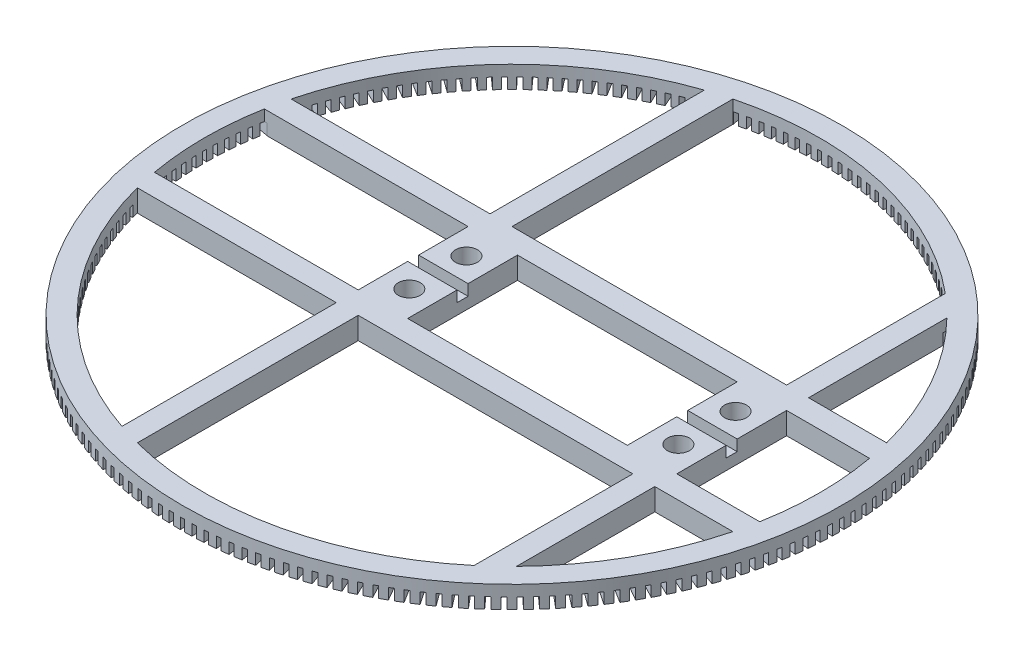
SolidWorks part; units mm, degrees
ref_plane "Front Plane" through (0, 0, 0) normal (0, 0, 1) x (1, 0, 0)
ref_plane "Top Plane" through (0, 0, 0) normal (0, 1, 0) x (1, 0, 0)
ref_plane "Right Plane" through (0, 0, 0) normal (1, 0, 0) x (0, 0, -1)
sketch "Sketch1" plane through (0, 0, 0) normal (0, 1, 0) x (1, 0, 0)
  line L0 (-20, 0) -> (-11, 0)
  line L1 (-20, -10) -> (20, -10)
  line L2 (-20, -10) -> (-20, 10)
  line L3 (-20, 10) -> (20, 10)
  line L4 (20, -10) -> (20, 10)
  line L5 (-20, -10) -> (20, 10) construction
  line L6 (-20, 10) -> (20, -10) construction
  line L7 (-20, 10) -> (-24.5, 10)
  line L8 (-29, -14) -> (29, -14)
  line L9 (-29, -14) -> (-29, 14)
  line L10 (-29, 14) -> (29, 14)
  line L11 (29, -14) -> (29, 14)
  line L12 (-29, -14) -> (29, 14) construction
  line L13 (-29, 14) -> (29, -14) construction
  line L14 (-24.5, 10) -> (-24.5, 5.2)
  line L15 (0, 0) -> (0, 10)
  line L16 (29, 14) -> (43.2218, 14)
  line L17 (29, -14) -> (43.2218, -14)
  line L18 (29, -10) -> (44.0999, -10)
  line L19 (29, 10) -> (44.0999, 10)
  line L20 (-29, 14) -> (-65.2218, 14)
  line L21 (-29, 10) -> (-66.0999, 10)
  line L22 (-29, -14) -> (-65.2218, -14)
  line L23 (-29, -10) -> (-66.0999, -10)
  line L24 (-29, 14) -> (-29, 53.0283)
  line L25 (-29, -14) -> (-29, -53.0283)
  line L26 (29, 14) -> (29, 39.1918)
  line L27 (29, -14) -> (29, -39.1918)
  line L28 (-25, 12.069) -> (-25, 54.2218)
  line L29 (25, -14) -> (25, -42.8952)
  line L30 (25, 14) -> (25, 42.8952)
  line L31 (-25, -14) -> (-25, -54.2218)
  line L32 (-25, -14) -> (-25, -53.0283) construction
  line L33 (25, -14) -> (25, -39.1918) construction
  line L34 (25, 14) -> (25, 39.1918) construction
  line L35 (-25, 14) -> (-25, 53.0283) construction
  circle A0 centre (-11, 0) radius 60
  circle A1 centre (-24.5, 5.2) radius 2
  circle A2 centre (-24.5, -5.2) radius 2
  circle A3 centre (24.5, -5.2) radius 2
  circle A4 centre (24.5, 5.2) radius 2
  circle A5 centre (-11, 0) radius 56
  point P0 (0, 0)
  point P9 (0, 0)
  dimension "D4" = 58
  dimension "D8" = 4
  dimension "D1" = 20
  dimension "D2" = 40
  dimension "D3" = 9
  dimension "D5" = 28
  dimension "D6" = 4.8
  dimension "D7" = 4.5
  dimension "D9" = 4
extrude "Boss-Extrude1" add sketch "Sketch1" along normal blind 4 contours L8 L11 L10 L9 A2 A1 L3 L4 L1 L2 A3 A4 | L29 A5 L27 L8 | L17 A5 L18 L11 | A0 A5 | L19 A5 L16 L11 | L26 A5 L30 L10 | L28 A5 L24 L10 | L20 A5 L21 L9 | L23 A5 L22 L9 | L25 A5 L31 L8 region at (-28.356, 0, 12) region at (-47.3441, 0, 11.992) region at (-26.99, 0, 33.8275) region at (26.9545, 0, 27.573) region at (-47.3441, 0, -11.992) region at (36.3454, 0, 11.9801) region at (-26.99, 0, -33.8275) region at (36.3454, 0, -11.9801) region at (26.9545, 0, -27.573) region at (-69.3029, 0, 0)
sketch "Sketch3" plane through (0, 4, 0) normal (0, 1, 0) x (1, 0, 0)
  line L0 (29, -10) -> (29, 10) construction
  line L1 (-29, -1) -> (29, -1)
  line L2 (-29, -1) -> (-29, 1)
  line L3 (-29, 1) -> (29, 1)
  line L4 (29, -1) -> (29, 1)
  line L5 (-29, -1) -> (29, 1) construction
  line L6 (-29, 1) -> (29, -1) construction
  point P0 (0, 0)
  dimension "D1" = 2
extrude "Cut-Extrude1" cut sketch "Sketch3" against normal blind 2
sketch "Sketch4" plane through (0, 0, 0) normal (0, -1, 0) x (1, 0, 0)
  line L0 (-71.4492, 2.5112) -> (-71.4771, 1.7117)
  line L1 (-71.5, 0.4) -> (-66.5, 0.4)
  line L2 (-71.5, 0.4) -> (-71.5, -0.4)
  line L3 (-71.5, -0.4) -> (-66.5, -0.4)
  line L4 (-66.5, 0.4) -> (-66.5, -0.4)
  line L5 (-71.5, 0.4) -> (-66.5, -0.4) construction
  line L6 (-71.5, -0.4) -> (-66.5, 0.4) construction
  line L7 (-71.4492, 2.5112) -> (-66.4522, 2.3367)
  line L8 (-66.4522, 2.3367) -> (-66.4802, 1.5372)
  line L9 (-71.4771, 1.7117) -> (-66.4802, 1.5372)
  line L10 (-71.3247, 4.6193) -> (-71.3805, 3.8212)
  line L11 (-71.3247, 4.6193) -> (-66.3369, 4.2705)
  line L12 (-66.3369, 4.2705) -> (-66.3927, 3.4725)
  line L13 (-71.3805, 3.8212) -> (-66.3927, 3.4725)
  line L14 (-71.1268, 6.7218) -> (-71.2104, 5.9262)
  line L15 (-71.1268, 6.7218) -> (-66.1542, 6.1991)
  line L16 (-66.1542, 6.1991) -> (-66.2378, 5.4035)
  line L17 (-71.2104, 5.9262) -> (-66.2378, 5.4035)
  line L18 (-70.8555, 8.8161) -> (-70.9669, 8.0239)
  line L19 (-70.8555, 8.8161) -> (-65.9042, 8.1202)
  line L20 (-65.9042, 8.1202) -> (-66.0155, 7.328)
  line L21 (-70.9669, 8.0239) -> (-66.0155, 7.328)
  line L22 (-70.5114, 10.8996) -> (-70.6503, 10.1118)
  line L23 (-70.5114, 10.8996) -> (-65.5874, 10.0314)
  line L24 (-65.5874, 10.0314) -> (-65.7263, 9.2436)
  line L25 (-70.6503, 10.1118) -> (-65.7263, 9.2436)
  line L26 (-70.0948, 12.9699) -> (-70.2611, 12.1874)
  line L27 (-70.0948, 12.9699) -> (-65.204, 11.9304)
  line L28 (-65.204, 11.9304) -> (-65.3704, 11.1478)
  line L29 (-70.2611, 12.1874) -> (-65.3704, 11.1478)
  line L30 (-69.6061, 15.0244) -> (-69.7997, 14.2482)
  line L31 (-69.6061, 15.0244) -> (-64.7546, 13.8148)
  line L32 (-64.7546, 13.8148) -> (-64.9482, 13.0385)
  line L33 (-69.7997, 14.2482) -> (-64.9482, 13.0385)
  line L34 (-69.0461, 17.0606) -> (-69.2666, 16.2916)
  line L35 (-69.0461, 17.0606) -> (-64.2398, 15.6824)
  line L36 (-64.2398, 15.6824) -> (-64.4603, 14.9134)
  line L37 (-69.2666, 16.2916) -> (-64.4603, 14.9134)
  line L38 (-68.4153, 19.076) -> (-68.6625, 18.3151)
  line L39 (-68.4153, 19.076) -> (-63.66, 17.5309)
  line L40 (-63.66, 17.5309) -> (-63.9072, 16.77)
  line L41 (-68.6625, 18.3151) -> (-63.9072, 16.77)
  line L42 (-67.7146, 21.0681) -> (-67.9882, 20.3163)
  line L43 (-67.7146, 21.0681) -> (-63.0161, 19.358)
  line L44 (-63.0161, 19.358) -> (-63.2897, 18.6062)
  line L45 (-67.9882, 20.3163) -> (-63.2897, 18.6062)
  line L46 (-66.9448, 23.0346) -> (-67.2445, 22.2928)
  line L47 (-66.9448, 23.0346) -> (-62.3089, 21.1615)
  line L48 (-62.3089, 21.1615) -> (-62.6085, 20.4198)
  line L49 (-67.2445, 22.2928) -> (-62.6085, 20.4198)
  line L50 (-66.1068, 24.973) -> (-66.4322, 24.2421)
  line L51 (-66.1068, 24.973) -> (-61.5391, 22.9393)
  line L52 (-61.5391, 22.9393) -> (-61.8645, 22.2085)
  line L53 (-66.4322, 24.2421) -> (-61.8645, 22.2085)
  line L54 (-65.2017, 26.881) -> (-65.5524, 26.1619)
  line L55 (-65.2017, 26.881) -> (-60.7077, 24.6891)
  line L56 (-60.7077, 24.6891) -> (-61.0584, 23.9701)
  line L57 (-65.5524, 26.1619) -> (-61.0584, 23.9701)
  line L58 (-64.2305, 28.7562) -> (-64.6061, 28.0499)
  line L59 (-64.2305, 28.7562) -> (-59.8158, 26.4089)
  line L60 (-59.8158, 26.4089) -> (-60.1914, 25.7025)
  line L61 (-64.6061, 28.0499) -> (-60.1914, 25.7025)
  line L62 (-63.1945, 30.5964) -> (-63.5945, 29.9036)
  line L63 (-63.1945, 30.5964) -> (-58.8644, 28.0964)
  line L64 (-58.8644, 28.0964) -> (-59.2644, 27.4036)
  line L65 (-63.5945, 29.9036) -> (-59.2644, 27.4036)
  line L66 (-62.0949, 32.3993) -> (-62.5189, 31.7209)
  line L67 (-62.0949, 32.3993) -> (-57.8547, 29.7497)
  line L68 (-57.8547, 29.7497) -> (-58.2786, 29.0713)
  line L69 (-62.5189, 31.7209) -> (-58.2786, 29.0713)
  line L70 (-60.9331, 34.1628) -> (-61.3805, 33.4996)
  line L71 (-60.9331, 34.1628) -> (-56.7879, 31.3668)
  line L72 (-56.7879, 31.3668) -> (-57.2353, 30.7036)
  line L73 (-61.3805, 33.4996) -> (-57.2353, 30.7036)
  line L74 (-59.7104, 35.8846) -> (-60.1806, 35.2374)
  line L75 (-59.7104, 35.8846) -> (-55.6653, 32.9457)
  line L76 (-55.6653, 32.9457) -> (-56.1356, 32.2985)
  line L77 (-60.1806, 35.2374) -> (-56.1356, 32.2985)
  line L78 (-58.4284, 37.5627) -> (-58.9209, 36.9323)
  line L79 (-58.4284, 37.5627) -> (-54.4883, 34.4844)
  line L80 (-54.4883, 34.4844) -> (-54.9809, 33.854)
  line L81 (-58.9209, 36.9323) -> (-54.9809, 33.854)
  line L82 (-57.0886, 39.1951) -> (-57.6028, 38.5822)
  line L83 (-57.0886, 39.1951) -> (-53.2584, 35.9811)
  line L84 (-53.2584, 35.9811) -> (-53.7726, 35.3683)
  line L85 (-57.6028, 38.5822) -> (-53.7726, 35.3683)
  line L86 (-55.6926, 40.7797) -> (-56.2279, 40.1851)
  line L87 (-55.6926, 40.7797) -> (-51.9769, 37.434)
  line L88 (-51.9769, 37.434) -> (-52.5122, 36.8395)
  line L89 (-56.2279, 40.1851) -> (-52.5122, 36.8395)
  line L90 (-54.2422, 42.3146) -> (-54.7979, 41.7391)
  line L91 (-54.2422, 42.3146) -> (-50.6455, 38.8413)
  line L92 (-50.6455, 38.8413) -> (-51.2012, 38.2658)
  line L93 (-54.7979, 41.7391) -> (-51.2012, 38.2658)
  line L94 (-52.7391, 43.7979) -> (-53.3146, 43.2422)
  line L95 (-52.7391, 43.7979) -> (-49.2658, 40.2012)
  line L96 (-49.2658, 40.2012) -> (-49.8413, 39.6455)
  line L97 (-53.3146, 43.2422) -> (-49.8413, 39.6455)
  line L98 (-51.1851, 45.2279) -> (-51.7797, 44.6926)
  line L99 (-51.1851, 45.2279) -> (-47.8395, 41.5122)
  line L100 (-47.8395, 41.5122) -> (-48.434, 40.9769)
  line L101 (-51.7797, 44.6926) -> (-48.434, 40.9769)
  line L102 (-49.5822, 46.6028) -> (-50.1951, 46.0886)
  line L103 (-49.5822, 46.6028) -> (-46.3683, 42.7726)
  line L104 (-46.3683, 42.7726) -> (-46.9811, 42.2584)
  line L105 (-50.1951, 46.0886) -> (-46.9811, 42.2584)
  line L106 (-47.9323, 47.9209) -> (-48.5627, 47.4284)
  line L107 (-47.9323, 47.9209) -> (-44.854, 43.9809)
  line L108 (-44.854, 43.9809) -> (-45.4844, 43.4883)
  line L109 (-48.5627, 47.4284) -> (-45.4844, 43.4883)
  line L110 (-46.2374, 49.1806) -> (-46.8846, 48.7104)
  line L111 (-46.2374, 49.1806) -> (-43.2985, 45.1356)
  line L112 (-43.2985, 45.1356) -> (-43.9457, 44.6653)
  line L113 (-46.8846, 48.7104) -> (-43.9457, 44.6653)
  line L114 (-44.4996, 50.3805) -> (-45.1628, 49.9331)
  line L115 (-44.4996, 50.3805) -> (-41.7036, 46.2353)
  line L116 (-41.7036, 46.2353) -> (-42.3668, 45.7879)
  line L117 (-45.1628, 49.9331) -> (-42.3668, 45.7879)
  line L118 (-42.7209, 51.5189) -> (-43.3993, 51.0949)
  line L119 (-42.7209, 51.5189) -> (-40.0713, 47.2786)
  line L120 (-40.0713, 47.2786) -> (-40.7497, 46.8547)
  line L121 (-43.3993, 51.0949) -> (-40.7497, 46.8547)
  line L122 (-40.9036, 52.5945) -> (-41.5964, 52.1945)
  line L123 (-40.9036, 52.5945) -> (-38.4036, 48.2644)
  line L124 (-38.4036, 48.2644) -> (-39.0964, 47.8644)
  line L125 (-41.5964, 52.1945) -> (-39.0964, 47.8644)
  line L126 (-39.0499, 53.6061) -> (-39.7562, 53.2305)
  line L127 (-39.0499, 53.6061) -> (-36.7025, 49.1914)
  line L128 (-36.7025, 49.1914) -> (-37.4089, 48.8158)
  line L129 (-39.7562, 53.2305) -> (-37.4089, 48.8158)
  line L130 (-37.1619, 54.5524) -> (-37.881, 54.2017)
  line L131 (-37.1619, 54.5524) -> (-34.9701, 50.0584)
  line L132 (-34.9701, 50.0584) -> (-35.6891, 49.7077)
  line L133 (-37.881, 54.2017) -> (-35.6891, 49.7077)
  line L134 (-35.2421, 55.4322) -> (-35.973, 55.1068)
  line L135 (-35.2421, 55.4322) -> (-33.2085, 50.8645)
  line L136 (-33.2085, 50.8645) -> (-33.9393, 50.5391)
  line L137 (-35.973, 55.1068) -> (-33.9393, 50.5391)
  line L138 (-33.2928, 56.2445) -> (-34.0346, 55.9448)
  line L139 (-33.2928, 56.2445) -> (-31.4198, 51.6085)
  line L140 (-31.4198, 51.6085) -> (-32.1615, 51.3089)
  line L141 (-34.0346, 55.9448) -> (-32.1615, 51.3089)
  line L142 (-31.3163, 56.9882) -> (-32.0681, 56.7146)
  line L143 (-31.3163, 56.9882) -> (-29.6062, 52.2897)
  line L144 (-29.6062, 52.2897) -> (-30.358, 52.0161)
  line L145 (-32.0681, 56.7146) -> (-30.358, 52.0161)
  line L146 (-29.3151, 57.6625) -> (-30.076, 57.4153)
  line L147 (-29.3151, 57.6625) -> (-27.77, 52.9072)
  line L148 (-27.77, 52.9072) -> (-28.5309, 52.66)
  line L149 (-30.076, 57.4153) -> (-28.5309, 52.66)
  line L150 (-27.2916, 58.2666) -> (-28.0606, 58.0461)
  line L151 (-27.2916, 58.2666) -> (-25.9134, 53.4603)
  line L152 (-25.9134, 53.4603) -> (-26.6824, 53.2398)
  line L153 (-28.0606, 58.0461) -> (-26.6824, 53.2398)
  line L154 (-25.2482, 58.7997) -> (-26.0244, 58.6061)
  line L155 (-25.2482, 58.7997) -> (-24.0385, 53.9482)
  line L156 (-24.0385, 53.9482) -> (-24.8148, 53.7546)
  line L157 (-26.0244, 58.6061) -> (-24.8148, 53.7546)
  line L158 (-23.1874, 59.2611) -> (-23.9699, 59.0948)
  line L159 (-23.1874, 59.2611) -> (-22.1478, 54.3704)
  line L160 (-22.1478, 54.3704) -> (-22.9304, 54.204)
  line L161 (-23.9699, 59.0948) -> (-22.9304, 54.204)
  line L162 (-21.1118, 59.6503) -> (-21.8996, 59.5114)
  line L163 (-21.1118, 59.6503) -> (-20.2436, 54.7263)
  line L164 (-20.2436, 54.7263) -> (-21.0314, 54.5874)
  line L165 (-21.8996, 59.5114) -> (-21.0314, 54.5874)
  line L166 (-19.0239, 59.9669) -> (-19.8161, 59.8555)
  line L167 (-19.0239, 59.9669) -> (-18.328, 55.0155)
  line L168 (-18.328, 55.0155) -> (-19.1202, 54.9042)
  line L169 (-19.8161, 59.8555) -> (-19.1202, 54.9042)
  line L170 (-16.9262, 60.2104) -> (-17.7218, 60.1268)
  line L171 (-16.9262, 60.2104) -> (-16.4035, 55.2378)
  line L172 (-16.4035, 55.2378) -> (-17.1991, 55.1542)
  line L173 (-17.7218, 60.1268) -> (-17.1991, 55.1542)
  line L174 (-14.8212, 60.3805) -> (-15.6193, 60.3247)
  line L175 (-14.8212, 60.3805) -> (-14.4725, 55.3927)
  line L176 (-14.4725, 55.3927) -> (-15.2705, 55.3369)
  line L177 (-15.6193, 60.3247) -> (-15.2705, 55.3369)
  line L178 (-12.7117, 60.4771) -> (-13.5112, 60.4492)
  line L179 (-12.7117, 60.4771) -> (-12.5372, 55.4802)
  line L180 (-12.5372, 55.4802) -> (-13.3367, 55.4522)
  line L181 (-13.5112, 60.4492) -> (-13.3367, 55.4522)
  line L182 (-10.6, 60.5) -> (-11.4, 60.5)
  line L183 (-10.6, 60.5) -> (-10.6, 55.5)
  line L184 (-10.6, 55.5) -> (-11.4, 55.5)
  line L185 (-11.4, 60.5) -> (-11.4, 55.5)
  line L186 (-8.4888, 60.4492) -> (-9.2883, 60.4771)
  line L187 (-8.4888, 60.4492) -> (-8.6633, 55.4522)
  line L188 (-8.6633, 55.4522) -> (-9.4628, 55.4802)
  line L189 (-9.2883, 60.4771) -> (-9.4628, 55.4802)
  line L190 (-6.3807, 60.3247) -> (-7.1788, 60.3805)
  line L191 (-6.3807, 60.3247) -> (-6.7295, 55.3369)
  line L192 (-6.7295, 55.3369) -> (-7.5275, 55.3927)
  line L193 (-7.1788, 60.3805) -> (-7.5275, 55.3927)
  line L194 (-4.2782, 60.1268) -> (-5.0738, 60.2104)
  line L195 (-4.2782, 60.1268) -> (-4.8009, 55.1542)
  line L196 (-4.8009, 55.1542) -> (-5.5965, 55.2378)
  line L197 (-5.0738, 60.2104) -> (-5.5965, 55.2378)
  line L198 (-2.1839, 59.8555) -> (-2.9761, 59.9669)
  line L199 (-2.1839, 59.8555) -> (-2.8798, 54.9042)
  line L200 (-2.8798, 54.9042) -> (-3.672, 55.0155)
  line L201 (-2.9761, 59.9669) -> (-3.672, 55.0155)
  line L202 (-0.1004, 59.5114) -> (-0.8882, 59.6503)
  line L203 (-0.1004, 59.5114) -> (-0.9686, 54.5874)
  line L204 (-0.9686, 54.5874) -> (-1.7564, 54.7263)
  line L205 (-0.8882, 59.6503) -> (-1.7564, 54.7263)
  line L206 (1.9699, 59.0948) -> (1.1874, 59.2611)
  line L207 (1.9699, 59.0948) -> (0.9304, 54.204)
  line L208 (0.9304, 54.204) -> (0.1478, 54.3704)
  line L209 (1.1874, 59.2611) -> (0.1478, 54.3704)
  line L210 (4.0244, 58.6061) -> (3.2482, 58.7997)
  line L211 (4.0244, 58.6061) -> (2.8148, 53.7546)
  line L212 (2.8148, 53.7546) -> (2.0385, 53.9482)
  line L213 (3.2482, 58.7997) -> (2.0385, 53.9482)
  line L214 (6.0606, 58.0461) -> (5.2916, 58.2666)
  line L215 (6.0606, 58.0461) -> (4.6824, 53.2398)
  line L216 (4.6824, 53.2398) -> (3.9134, 53.4603)
  line L217 (5.2916, 58.2666) -> (3.9134, 53.4603)
  line L218 (8.076, 57.4153) -> (7.3151, 57.6625)
  line L219 (8.076, 57.4153) -> (6.5309, 52.66)
  line L220 (6.5309, 52.66) -> (5.77, 52.9072)
  line L221 (7.3151, 57.6625) -> (5.77, 52.9072)
  line L222 (10.0681, 56.7146) -> (9.3163, 56.9882)
  line L223 (10.0681, 56.7146) -> (8.358, 52.0161)
  line L224 (8.358, 52.0161) -> (7.6062, 52.2897)
  line L225 (9.3163, 56.9882) -> (7.6062, 52.2897)
  line L226 (12.0346, 55.9448) -> (11.2928, 56.2445)
  line L227 (12.0346, 55.9448) -> (10.1615, 51.3089)
  line L228 (10.1615, 51.3089) -> (9.4198, 51.6085)
  line L229 (11.2928, 56.2445) -> (9.4198, 51.6085)
  line L230 (13.973, 55.1068) -> (13.2421, 55.4322)
  line L231 (13.973, 55.1068) -> (11.9393, 50.5391)
  line L232 (11.9393, 50.5391) -> (11.2085, 50.8645)
  line L233 (13.2421, 55.4322) -> (11.2085, 50.8645)
  line L234 (15.881, 54.2017) -> (15.1619, 54.5524)
  line L235 (15.881, 54.2017) -> (13.6891, 49.7077)
  line L236 (13.6891, 49.7077) -> (12.9701, 50.0584)
  line L237 (15.1619, 54.5524) -> (12.9701, 50.0584)
  line L238 (17.7562, 53.2305) -> (17.0499, 53.6061)
  line L239 (17.7562, 53.2305) -> (15.4089, 48.8158)
  line L240 (15.4089, 48.8158) -> (14.7025, 49.1914)
  line L241 (17.0499, 53.6061) -> (14.7025, 49.1914)
  line L242 (19.5964, 52.1945) -> (18.9036, 52.5945)
  line L243 (19.5964, 52.1945) -> (17.0964, 47.8644)
  line L244 (17.0964, 47.8644) -> (16.4036, 48.2644)
  line L245 (18.9036, 52.5945) -> (16.4036, 48.2644)
  line L246 (21.3993, 51.0949) -> (20.7209, 51.5189)
  line L247 (21.3993, 51.0949) -> (18.7497, 46.8547)
  line L248 (18.7497, 46.8547) -> (18.0713, 47.2786)
  line L249 (20.7209, 51.5189) -> (18.0713, 47.2786)
  line L250 (23.1628, 49.9331) -> (22.4996, 50.3805)
  line L251 (23.1628, 49.9331) -> (20.3668, 45.7879)
  line L252 (20.3668, 45.7879) -> (19.7036, 46.2353)
  line L253 (22.4996, 50.3805) -> (19.7036, 46.2353)
  line L254 (24.8846, 48.7104) -> (24.2374, 49.1806)
  line L255 (24.8846, 48.7104) -> (21.9457, 44.6653)
  line L256 (21.9457, 44.6653) -> (21.2985, 45.1356)
  line L257 (24.2374, 49.1806) -> (21.2985, 45.1356)
  line L258 (26.5627, 47.4284) -> (25.9323, 47.9209)
  line L259 (26.5627, 47.4284) -> (23.4844, 43.4883)
  line L260 (23.4844, 43.4883) -> (22.854, 43.9809)
  line L261 (25.9323, 47.9209) -> (22.854, 43.9809)
  line L262 (28.1951, 46.0886) -> (27.5822, 46.6028)
  line L263 (28.1951, 46.0886) -> (24.9811, 42.2584)
  line L264 (24.9811, 42.2584) -> (24.3683, 42.7726)
  line L265 (27.5822, 46.6028) -> (24.3683, 42.7726)
  line L266 (29.7797, 44.6926) -> (29.1851, 45.2279)
  line L267 (29.7797, 44.6926) -> (26.434, 40.9769)
  line L268 (26.434, 40.9769) -> (25.8395, 41.5122)
  line L269 (29.1851, 45.2279) -> (25.8395, 41.5122)
  line L270 (31.3146, 43.2422) -> (30.7391, 43.7979)
  line L271 (31.3146, 43.2422) -> (27.8413, 39.6455)
  line L272 (27.8413, 39.6455) -> (27.2658, 40.2012)
  line L273 (30.7391, 43.7979) -> (27.2658, 40.2012)
  line L274 (32.7979, 41.7391) -> (32.2422, 42.3146)
  line L275 (32.7979, 41.7391) -> (29.2012, 38.2658)
  line L276 (29.2012, 38.2658) -> (28.6455, 38.8413)
  line L277 (32.2422, 42.3146) -> (28.6455, 38.8413)
  line L278 (34.2279, 40.1851) -> (33.6926, 40.7797)
  line L279 (34.2279, 40.1851) -> (30.5122, 36.8395)
  line L280 (30.5122, 36.8395) -> (29.9769, 37.434)
  line L281 (33.6926, 40.7797) -> (29.9769, 37.434)
  line L282 (35.6028, 38.5822) -> (35.0886, 39.1951)
  line L283 (35.6028, 38.5822) -> (31.7726, 35.3683)
  line L284 (31.7726, 35.3683) -> (31.2584, 35.9811)
  line L285 (35.0886, 39.1951) -> (31.2584, 35.9811)
  line L286 (36.9209, 36.9323) -> (36.4284, 37.5627)
  line L287 (36.9209, 36.9323) -> (32.9809, 33.854)
  line L288 (32.9809, 33.854) -> (32.4883, 34.4844)
  line L289 (36.4284, 37.5627) -> (32.4883, 34.4844)
  line L290 (38.1806, 35.2374) -> (37.7104, 35.8846)
  line L291 (38.1806, 35.2374) -> (34.1356, 32.2985)
  line L292 (34.1356, 32.2985) -> (33.6653, 32.9457)
  line L293 (37.7104, 35.8846) -> (33.6653, 32.9457)
  line L294 (39.3805, 33.4996) -> (38.9331, 34.1628)
  line L295 (39.3805, 33.4996) -> (35.2353, 30.7036)
  line L296 (35.2353, 30.7036) -> (34.7879, 31.3668)
  line L297 (38.9331, 34.1628) -> (34.7879, 31.3668)
  line L298 (40.5189, 31.7209) -> (40.0949, 32.3993)
  line L299 (40.5189, 31.7209) -> (36.2786, 29.0713)
  line L300 (36.2786, 29.0713) -> (35.8547, 29.7497)
  line L301 (40.0949, 32.3993) -> (35.8547, 29.7497)
  line L302 (41.5945, 29.9036) -> (41.1945, 30.5964)
  line L303 (41.5945, 29.9036) -> (37.2644, 27.4036)
  line L304 (37.2644, 27.4036) -> (36.8644, 28.0964)
  line L305 (41.1945, 30.5964) -> (36.8644, 28.0964)
  line L306 (42.6061, 28.0499) -> (42.2305, 28.7562)
  line L307 (42.6061, 28.0499) -> (38.1914, 25.7025)
  line L308 (38.1914, 25.7025) -> (37.8158, 26.4089)
  line L309 (42.2305, 28.7562) -> (37.8158, 26.4089)
  line L310 (43.5524, 26.1619) -> (43.2017, 26.881)
  line L311 (43.5524, 26.1619) -> (39.0584, 23.9701)
  line L312 (39.0584, 23.9701) -> (38.7077, 24.6891)
  line L313 (43.2017, 26.881) -> (38.7077, 24.6891)
  line L314 (44.4322, 24.2421) -> (44.1068, 24.973)
  line L315 (44.4322, 24.2421) -> (39.8645, 22.2085)
  line L316 (39.8645, 22.2085) -> (39.5391, 22.9393)
  line L317 (44.1068, 24.973) -> (39.5391, 22.9393)
  line L318 (45.2445, 22.2928) -> (44.9448, 23.0346)
  line L319 (45.2445, 22.2928) -> (40.6085, 20.4198)
  line L320 (40.6085, 20.4198) -> (40.3089, 21.1615)
  line L321 (44.9448, 23.0346) -> (40.3089, 21.1615)
  line L322 (45.9882, 20.3163) -> (45.7146, 21.0681)
  line L323 (45.9882, 20.3163) -> (41.2897, 18.6062)
  line L324 (41.2897, 18.6062) -> (41.0161, 19.358)
  line L325 (45.7146, 21.0681) -> (41.0161, 19.358)
  line L326 (46.6625, 18.3151) -> (46.4153, 19.076)
  line L327 (46.6625, 18.3151) -> (41.9072, 16.77)
  line L328 (41.9072, 16.77) -> (41.66, 17.5309)
  line L329 (46.4153, 19.076) -> (41.66, 17.5309)
  line L330 (47.2666, 16.2916) -> (47.0461, 17.0606)
  line L331 (47.2666, 16.2916) -> (42.4603, 14.9134)
  line L332 (42.4603, 14.9134) -> (42.2398, 15.6824)
  line L333 (47.0461, 17.0606) -> (42.2398, 15.6824)
  line L334 (47.7997, 14.2482) -> (47.6061, 15.0244)
  line L335 (47.7997, 14.2482) -> (42.9482, 13.0385)
  line L336 (42.9482, 13.0385) -> (42.7546, 13.8148)
  line L337 (47.6061, 15.0244) -> (42.7546, 13.8148)
  line L338 (48.2611, 12.1874) -> (48.0948, 12.9699)
  line L339 (48.2611, 12.1874) -> (43.3704, 11.1478)
  line L340 (43.3704, 11.1478) -> (43.204, 11.9304)
  line L341 (48.0948, 12.9699) -> (43.204, 11.9304)
  line L342 (48.6503, 10.1118) -> (48.5114, 10.8996)
  line L343 (48.6503, 10.1118) -> (43.7263, 9.2436)
  line L344 (43.7263, 9.2436) -> (43.5874, 10.0314)
  line L345 (48.5114, 10.8996) -> (43.5874, 10.0314)
  line L346 (48.9669, 8.0239) -> (48.8555, 8.8161)
  line L347 (48.9669, 8.0239) -> (44.0155, 7.328)
  line L348 (44.0155, 7.328) -> (43.9042, 8.1202)
  line L349 (48.8555, 8.8161) -> (43.9042, 8.1202)
  line L350 (49.2104, 5.9262) -> (49.1268, 6.7218)
  line L351 (49.2104, 5.9262) -> (44.2378, 5.4035)
  line L352 (44.2378, 5.4035) -> (44.1542, 6.1991)
  line L353 (49.1268, 6.7218) -> (44.1542, 6.1991)
  line L354 (49.3805, 3.8212) -> (49.3247, 4.6193)
  line L355 (49.3805, 3.8212) -> (44.3927, 3.4725)
  line L356 (44.3927, 3.4725) -> (44.3369, 4.2705)
  line L357 (49.3247, 4.6193) -> (44.3369, 4.2705)
  line L358 (49.4771, 1.7117) -> (49.4492, 2.5112)
  line L359 (49.4771, 1.7117) -> (44.4802, 1.5372)
  line L360 (44.4802, 1.5372) -> (44.4522, 2.3367)
  line L361 (49.4492, 2.5112) -> (44.4522, 2.3367)
  line L362 (49.5, -0.4) -> (49.5, 0.4)
  line L363 (49.5, -0.4) -> (44.5, -0.4)
  line L364 (44.5, -0.4) -> (44.5, 0.4)
  line L365 (49.5, 0.4) -> (44.5, 0.4)
  line L366 (49.4492, -2.5112) -> (49.4771, -1.7117)
  line L367 (49.4492, -2.5112) -> (44.4522, -2.3367)
  line L368 (44.4522, -2.3367) -> (44.4802, -1.5372)
  line L369 (49.4771, -1.7117) -> (44.4802, -1.5372)
  line L370 (49.3247, -4.6193) -> (49.3805, -3.8212)
  line L371 (49.3247, -4.6193) -> (44.3369, -4.2705)
  line L372 (44.3369, -4.2705) -> (44.3927, -3.4725)
  line L373 (49.3805, -3.8212) -> (44.3927, -3.4725)
  line L374 (49.1268, -6.7218) -> (49.2104, -5.9262)
  line L375 (49.1268, -6.7218) -> (44.1542, -6.1991)
  line L376 (44.1542, -6.1991) -> (44.2378, -5.4035)
  line L377 (49.2104, -5.9262) -> (44.2378, -5.4035)
  line L378 (48.8555, -8.8161) -> (48.9669, -8.0239)
  line L379 (48.8555, -8.8161) -> (43.9042, -8.1202)
  line L380 (43.9042, -8.1202) -> (44.0155, -7.328)
  line L381 (48.9669, -8.0239) -> (44.0155, -7.328)
  line L382 (48.5114, -10.8996) -> (48.6503, -10.1118)
  line L383 (48.5114, -10.8996) -> (43.5874, -10.0314)
  line L384 (43.5874, -10.0314) -> (43.7263, -9.2436)
  line L385 (48.6503, -10.1118) -> (43.7263, -9.2436)
  line L386 (48.0948, -12.9699) -> (48.2611, -12.1874)
  line L387 (48.0948, -12.9699) -> (43.204, -11.9304)
  line L388 (43.204, -11.9304) -> (43.3704, -11.1478)
  line L389 (48.2611, -12.1874) -> (43.3704, -11.1478)
  line L390 (47.6061, -15.0244) -> (47.7997, -14.2482)
  line L391 (47.6061, -15.0244) -> (42.7546, -13.8148)
  line L392 (42.7546, -13.8148) -> (42.9482, -13.0385)
  line L393 (47.7997, -14.2482) -> (42.9482, -13.0385)
  line L394 (47.0461, -17.0606) -> (47.2666, -16.2916)
  line L395 (47.0461, -17.0606) -> (42.2398, -15.6824)
  line L396 (42.2398, -15.6824) -> (42.4603, -14.9134)
  line L397 (47.2666, -16.2916) -> (42.4603, -14.9134)
  line L398 (46.4153, -19.076) -> (46.6625, -18.3151)
  line L399 (46.4153, -19.076) -> (41.66, -17.5309)
  line L400 (41.66, -17.5309) -> (41.9072, -16.77)
  line L401 (46.6625, -18.3151) -> (41.9072, -16.77)
  line L402 (45.7146, -21.0681) -> (45.9882, -20.3163)
  line L403 (45.7146, -21.0681) -> (41.0161, -19.358)
  line L404 (41.0161, -19.358) -> (41.2897, -18.6062)
  line L405 (45.9882, -20.3163) -> (41.2897, -18.6062)
  line L406 (44.9448, -23.0346) -> (45.2445, -22.2928)
  line L407 (44.9448, -23.0346) -> (40.3089, -21.1615)
  line L408 (40.3089, -21.1615) -> (40.6085, -20.4198)
  line L409 (45.2445, -22.2928) -> (40.6085, -20.4198)
  line L410 (44.1068, -24.973) -> (44.4322, -24.2421)
  line L411 (44.1068, -24.973) -> (39.5391, -22.9393)
  line L412 (39.5391, -22.9393) -> (39.8645, -22.2085)
  line L413 (44.4322, -24.2421) -> (39.8645, -22.2085)
  line L414 (43.2017, -26.881) -> (43.5524, -26.1619)
  line L415 (43.2017, -26.881) -> (38.7077, -24.6891)
  line L416 (38.7077, -24.6891) -> (39.0584, -23.9701)
  line L417 (43.5524, -26.1619) -> (39.0584, -23.9701)
  line L418 (42.2305, -28.7562) -> (42.6061, -28.0499)
  line L419 (42.2305, -28.7562) -> (37.8158, -26.4089)
  line L420 (37.8158, -26.4089) -> (38.1914, -25.7025)
  line L421 (42.6061, -28.0499) -> (38.1914, -25.7025)
  line L422 (41.1945, -30.5964) -> (41.5945, -29.9036)
  line L423 (41.1945, -30.5964) -> (36.8644, -28.0964)
  line L424 (36.8644, -28.0964) -> (37.2644, -27.4036)
  line L425 (41.5945, -29.9036) -> (37.2644, -27.4036)
  line L426 (40.0949, -32.3993) -> (40.5189, -31.7209)
  line L427 (40.0949, -32.3993) -> (35.8547, -29.7497)
  line L428 (35.8547, -29.7497) -> (36.2786, -29.0713)
  line L429 (40.5189, -31.7209) -> (36.2786, -29.0713)
  line L430 (38.9331, -34.1628) -> (39.3805, -33.4996)
  line L431 (38.9331, -34.1628) -> (34.7879, -31.3668)
  line L432 (34.7879, -31.3668) -> (35.2353, -30.7036)
  line L433 (39.3805, -33.4996) -> (35.2353, -30.7036)
  line L434 (37.7104, -35.8846) -> (38.1806, -35.2374)
  line L435 (37.7104, -35.8846) -> (33.6653, -32.9457)
  line L436 (33.6653, -32.9457) -> (34.1356, -32.2985)
  line L437 (38.1806, -35.2374) -> (34.1356, -32.2985)
  line L438 (36.4284, -37.5627) -> (36.9209, -36.9323)
  line L439 (36.4284, -37.5627) -> (32.4883, -34.4844)
  line L440 (32.4883, -34.4844) -> (32.9809, -33.854)
  line L441 (36.9209, -36.9323) -> (32.9809, -33.854)
  line L442 (35.0886, -39.1951) -> (35.6028, -38.5822)
  line L443 (35.0886, -39.1951) -> (31.2584, -35.9811)
  line L444 (31.2584, -35.9811) -> (31.7726, -35.3683)
  line L445 (35.6028, -38.5822) -> (31.7726, -35.3683)
  line L446 (33.6926, -40.7797) -> (34.2279, -40.1851)
  line L447 (33.6926, -40.7797) -> (29.9769, -37.434)
  line L448 (29.9769, -37.434) -> (30.5122, -36.8395)
  line L449 (34.2279, -40.1851) -> (30.5122, -36.8395)
  line L450 (32.2422, -42.3146) -> (32.7979, -41.7391)
  line L451 (32.2422, -42.3146) -> (28.6455, -38.8413)
  line L452 (28.6455, -38.8413) -> (29.2012, -38.2658)
  line L453 (32.7979, -41.7391) -> (29.2012, -38.2658)
  line L454 (30.7391, -43.7979) -> (31.3146, -43.2422)
  line L455 (30.7391, -43.7979) -> (27.2658, -40.2012)
  line L456 (27.2658, -40.2012) -> (27.8413, -39.6455)
  line L457 (31.3146, -43.2422) -> (27.8413, -39.6455)
  line L458 (29.1851, -45.2279) -> (29.7797, -44.6926)
  line L459 (29.1851, -45.2279) -> (25.8395, -41.5122)
  line L460 (25.8395, -41.5122) -> (26.434, -40.9769)
  line L461 (29.7797, -44.6926) -> (26.434, -40.9769)
  line L462 (27.5822, -46.6028) -> (28.1951, -46.0886)
  line L463 (27.5822, -46.6028) -> (24.3683, -42.7726)
  line L464 (24.3683, -42.7726) -> (24.9811, -42.2584)
  line L465 (28.1951, -46.0886) -> (24.9811, -42.2584)
  line L466 (25.9323, -47.9209) -> (26.5627, -47.4284)
  line L467 (25.9323, -47.9209) -> (22.854, -43.9809)
  line L468 (22.854, -43.9809) -> (23.4844, -43.4883)
  line L469 (26.5627, -47.4284) -> (23.4844, -43.4883)
  line L470 (24.2374, -49.1806) -> (24.8846, -48.7104)
  line L471 (24.2374, -49.1806) -> (21.2985, -45.1356)
  line L472 (21.2985, -45.1356) -> (21.9457, -44.6653)
  line L473 (24.8846, -48.7104) -> (21.9457, -44.6653)
  line L474 (22.4996, -50.3805) -> (23.1628, -49.9331)
  line L475 (22.4996, -50.3805) -> (19.7036, -46.2353)
  line L476 (19.7036, -46.2353) -> (20.3668, -45.7879)
  line L477 (23.1628, -49.9331) -> (20.3668, -45.7879)
  line L478 (20.7209, -51.5189) -> (21.3993, -51.0949)
  line L479 (20.7209, -51.5189) -> (18.0713, -47.2786)
  line L480 (18.0713, -47.2786) -> (18.7497, -46.8547)
  line L481 (21.3993, -51.0949) -> (18.7497, -46.8547)
  line L482 (18.9036, -52.5945) -> (19.5964, -52.1945)
  line L483 (18.9036, -52.5945) -> (16.4036, -48.2644)
  line L484 (16.4036, -48.2644) -> (17.0964, -47.8644)
  line L485 (19.5964, -52.1945) -> (17.0964, -47.8644)
  line L486 (17.0499, -53.6061) -> (17.7562, -53.2305)
  line L487 (17.0499, -53.6061) -> (14.7025, -49.1914)
  line L488 (14.7025, -49.1914) -> (15.4089, -48.8158)
  line L489 (17.7562, -53.2305) -> (15.4089, -48.8158)
  line L490 (15.1619, -54.5524) -> (15.881, -54.2017)
  line L491 (15.1619, -54.5524) -> (12.9701, -50.0584)
  line L492 (12.9701, -50.0584) -> (13.6891, -49.7077)
  line L493 (15.881, -54.2017) -> (13.6891, -49.7077)
  line L494 (13.2421, -55.4322) -> (13.973, -55.1068)
  line L495 (13.2421, -55.4322) -> (11.2085, -50.8645)
  line L496 (11.2085, -50.8645) -> (11.9393, -50.5391)
  line L497 (13.973, -55.1068) -> (11.9393, -50.5391)
  line L498 (11.2928, -56.2445) -> (12.0346, -55.9448)
  line L499 (11.2928, -56.2445) -> (9.4198, -51.6085)
  line L500 (9.4198, -51.6085) -> (10.1615, -51.3089)
  line L501 (12.0346, -55.9448) -> (10.1615, -51.3089)
  line L502 (9.3163, -56.9882) -> (10.0681, -56.7146)
  line L503 (9.3163, -56.9882) -> (7.6062, -52.2897)
  line L504 (7.6062, -52.2897) -> (8.358, -52.0161)
  line L505 (10.0681, -56.7146) -> (8.358, -52.0161)
  line L506 (7.3151, -57.6625) -> (8.076, -57.4153)
  line L507 (7.3151, -57.6625) -> (5.77, -52.9072)
  line L508 (5.77, -52.9072) -> (6.5309, -52.66)
  line L509 (8.076, -57.4153) -> (6.5309, -52.66)
  line L510 (5.2916, -58.2666) -> (6.0606, -58.0461)
  line L511 (5.2916, -58.2666) -> (3.9134, -53.4603)
  line L512 (3.9134, -53.4603) -> (4.6824, -53.2398)
  line L513 (6.0606, -58.0461) -> (4.6824, -53.2398)
  line L514 (3.2482, -58.7997) -> (4.0244, -58.6061)
  line L515 (3.2482, -58.7997) -> (2.0385, -53.9482)
  line L516 (2.0385, -53.9482) -> (2.8148, -53.7546)
  line L517 (4.0244, -58.6061) -> (2.8148, -53.7546)
  line L518 (1.1874, -59.2611) -> (1.9699, -59.0948)
  line L519 (1.1874, -59.2611) -> (0.1478, -54.3704)
  line L520 (0.1478, -54.3704) -> (0.9304, -54.204)
  line L521 (1.9699, -59.0948) -> (0.9304, -54.204)
  line L522 (-0.8882, -59.6503) -> (-0.1004, -59.5114)
  line L523 (-0.8882, -59.6503) -> (-1.7564, -54.7263)
  line L524 (-1.7564, -54.7263) -> (-0.9686, -54.5874)
  line L525 (-0.1004, -59.5114) -> (-0.9686, -54.5874)
  line L526 (-2.9761, -59.9669) -> (-2.1839, -59.8555)
  line L527 (-2.9761, -59.9669) -> (-3.672, -55.0155)
  line L528 (-3.672, -55.0155) -> (-2.8798, -54.9042)
  line L529 (-2.1839, -59.8555) -> (-2.8798, -54.9042)
  line L530 (-5.0738, -60.2104) -> (-4.2782, -60.1268)
  line L531 (-5.0738, -60.2104) -> (-5.5965, -55.2378)
  line L532 (-5.5965, -55.2378) -> (-4.8009, -55.1542)
  line L533 (-4.2782, -60.1268) -> (-4.8009, -55.1542)
  line L534 (-7.1788, -60.3805) -> (-6.3807, -60.3247)
  line L535 (-7.1788, -60.3805) -> (-7.5275, -55.3927)
  line L536 (-7.5275, -55.3927) -> (-6.7295, -55.3369)
  line L537 (-6.3807, -60.3247) -> (-6.7295, -55.3369)
  line L538 (-9.2883, -60.4771) -> (-8.4888, -60.4492)
  line L539 (-9.2883, -60.4771) -> (-9.4628, -55.4802)
  line L540 (-9.4628, -55.4802) -> (-8.6633, -55.4522)
  line L541 (-8.4888, -60.4492) -> (-8.6633, -55.4522)
  line L542 (-11.4, -60.5) -> (-10.6, -60.5)
  line L543 (-11.4, -60.5) -> (-11.4, -55.5)
  line L544 (-11.4, -55.5) -> (-10.6, -55.5)
  line L545 (-10.6, -60.5) -> (-10.6, -55.5)
  line L546 (-13.5112, -60.4492) -> (-12.7117, -60.4771)
  line L547 (-13.5112, -60.4492) -> (-13.3367, -55.4522)
  line L548 (-13.3367, -55.4522) -> (-12.5372, -55.4802)
  line L549 (-12.7117, -60.4771) -> (-12.5372, -55.4802)
  line L550 (-15.6193, -60.3247) -> (-14.8212, -60.3805)
  line L551 (-15.6193, -60.3247) -> (-15.2705, -55.3369)
  line L552 (-15.2705, -55.3369) -> (-14.4725, -55.3927)
  line L553 (-14.8212, -60.3805) -> (-14.4725, -55.3927)
  line L554 (-17.7218, -60.1268) -> (-16.9262, -60.2104)
  line L555 (-17.7218, -60.1268) -> (-17.1991, -55.1542)
  line L556 (-17.1991, -55.1542) -> (-16.4035, -55.2378)
  line L557 (-16.9262, -60.2104) -> (-16.4035, -55.2378)
  line L558 (-19.8161, -59.8555) -> (-19.0239, -59.9669)
  line L559 (-19.8161, -59.8555) -> (-19.1202, -54.9042)
  line L560 (-19.1202, -54.9042) -> (-18.328, -55.0155)
  line L561 (-19.0239, -59.9669) -> (-18.328, -55.0155)
  line L562 (-21.8996, -59.5114) -> (-21.1118, -59.6503)
  line L563 (-21.8996, -59.5114) -> (-21.0314, -54.5874)
  line L564 (-21.0314, -54.5874) -> (-20.2436, -54.7263)
  line L565 (-21.1118, -59.6503) -> (-20.2436, -54.7263)
  line L566 (-23.9699, -59.0948) -> (-23.1874, -59.2611)
  line L567 (-23.9699, -59.0948) -> (-22.9304, -54.204)
  line L568 (-22.9304, -54.204) -> (-22.1478, -54.3704)
  line L569 (-23.1874, -59.2611) -> (-22.1478, -54.3704)
  line L570 (-26.0244, -58.6061) -> (-25.2482, -58.7997)
  line L571 (-26.0244, -58.6061) -> (-24.8148, -53.7546)
  line L572 (-24.8148, -53.7546) -> (-24.0385, -53.9482)
  line L573 (-25.2482, -58.7997) -> (-24.0385, -53.9482)
  line L574 (-28.0606, -58.0461) -> (-27.2916, -58.2666)
  line L575 (-28.0606, -58.0461) -> (-26.6824, -53.2398)
  line L576 (-26.6824, -53.2398) -> (-25.9134, -53.4603)
  line L577 (-27.2916, -58.2666) -> (-25.9134, -53.4603)
  line L578 (-30.076, -57.4153) -> (-29.3151, -57.6625)
  line L579 (-30.076, -57.4153) -> (-28.5309, -52.66)
  line L580 (-28.5309, -52.66) -> (-27.77, -52.9072)
  line L581 (-29.3151, -57.6625) -> (-27.77, -52.9072)
  line L582 (-32.0681, -56.7146) -> (-31.3163, -56.9882)
  line L583 (-32.0681, -56.7146) -> (-30.358, -52.0161)
  line L584 (-30.358, -52.0161) -> (-29.6062, -52.2897)
  line L585 (-31.3163, -56.9882) -> (-29.6062, -52.2897)
  line L586 (-34.0346, -55.9448) -> (-33.2928, -56.2445)
  line L587 (-34.0346, -55.9448) -> (-32.1615, -51.3089)
  line L588 (-32.1615, -51.3089) -> (-31.4198, -51.6085)
  line L589 (-33.2928, -56.2445) -> (-31.4198, -51.6085)
  line L590 (-35.973, -55.1068) -> (-35.2421, -55.4322)
  line L591 (-35.973, -55.1068) -> (-33.9393, -50.5391)
  line L592 (-33.9393, -50.5391) -> (-33.2085, -50.8645)
  line L593 (-35.2421, -55.4322) -> (-33.2085, -50.8645)
  line L594 (-37.881, -54.2017) -> (-37.1619, -54.5524)
  line L595 (-37.881, -54.2017) -> (-35.6891, -49.7077)
  line L596 (-35.6891, -49.7077) -> (-34.9701, -50.0584)
  line L597 (-37.1619, -54.5524) -> (-34.9701, -50.0584)
  line L598 (-39.7562, -53.2305) -> (-39.0499, -53.6061)
  line L599 (-39.7562, -53.2305) -> (-37.4089, -48.8158)
  line L600 (-37.4089, -48.8158) -> (-36.7025, -49.1914)
  line L601 (-39.0499, -53.6061) -> (-36.7025, -49.1914)
  line L602 (-41.5964, -52.1945) -> (-40.9036, -52.5945)
  line L603 (-41.5964, -52.1945) -> (-39.0964, -47.8644)
  line L604 (-39.0964, -47.8644) -> (-38.4036, -48.2644)
  line L605 (-40.9036, -52.5945) -> (-38.4036, -48.2644)
  line L606 (-43.3993, -51.0949) -> (-42.7209, -51.5189)
  line L607 (-43.3993, -51.0949) -> (-40.7497, -46.8547)
  line L608 (-40.7497, -46.8547) -> (-40.0713, -47.2786)
  line L609 (-42.7209, -51.5189) -> (-40.0713, -47.2786)
  line L610 (-45.1628, -49.9331) -> (-44.4996, -50.3805)
  line L611 (-45.1628, -49.9331) -> (-42.3668, -45.7879)
  line L612 (-42.3668, -45.7879) -> (-41.7036, -46.2353)
  line L613 (-44.4996, -50.3805) -> (-41.7036, -46.2353)
  line L614 (-46.8846, -48.7104) -> (-46.2374, -49.1806)
  line L615 (-46.8846, -48.7104) -> (-43.9457, -44.6653)
  line L616 (-43.9457, -44.6653) -> (-43.2985, -45.1356)
  line L617 (-46.2374, -49.1806) -> (-43.2985, -45.1356)
  line L618 (-48.5627, -47.4284) -> (-47.9323, -47.9209)
  line L619 (-48.5627, -47.4284) -> (-45.4844, -43.4883)
  line L620 (-45.4844, -43.4883) -> (-44.854, -43.9809)
  line L621 (-47.9323, -47.9209) -> (-44.854, -43.9809)
  line L622 (-50.1951, -46.0886) -> (-49.5822, -46.6028)
  line L623 (-50.1951, -46.0886) -> (-46.9811, -42.2584)
  line L624 (-46.9811, -42.2584) -> (-46.3683, -42.7726)
  line L625 (-49.5822, -46.6028) -> (-46.3683, -42.7726)
  line L626 (-51.7797, -44.6926) -> (-51.1851, -45.2279)
  line L627 (-51.7797, -44.6926) -> (-48.434, -40.9769)
  line L628 (-48.434, -40.9769) -> (-47.8395, -41.5122)
  line L629 (-51.1851, -45.2279) -> (-47.8395, -41.5122)
  line L630 (-53.3146, -43.2422) -> (-52.7391, -43.7979)
  line L631 (-53.3146, -43.2422) -> (-49.8413, -39.6455)
  line L632 (-49.8413, -39.6455) -> (-49.2658, -40.2012)
  line L633 (-52.7391, -43.7979) -> (-49.2658, -40.2012)
  line L634 (-54.7979, -41.7391) -> (-54.2422, -42.3146)
  line L635 (-54.7979, -41.7391) -> (-51.2012, -38.2658)
  line L636 (-51.2012, -38.2658) -> (-50.6455, -38.8413)
  line L637 (-54.2422, -42.3146) -> (-50.6455, -38.8413)
  line L638 (-56.2279, -40.1851) -> (-55.6926, -40.7797)
  line L639 (-56.2279, -40.1851) -> (-52.5122, -36.8395)
  line L640 (-52.5122, -36.8395) -> (-51.9769, -37.434)
  line L641 (-55.6926, -40.7797) -> (-51.9769, -37.434)
  line L642 (-57.6028, -38.5822) -> (-57.0886, -39.1951)
  line L643 (-57.6028, -38.5822) -> (-53.7726, -35.3683)
  line L644 (-53.7726, -35.3683) -> (-53.2584, -35.9811)
  line L645 (-57.0886, -39.1951) -> (-53.2584, -35.9811)
  line L646 (-58.9209, -36.9323) -> (-58.4284, -37.5627)
  line L647 (-58.9209, -36.9323) -> (-54.9809, -33.854)
  line L648 (-54.9809, -33.854) -> (-54.4883, -34.4844)
  line L649 (-58.4284, -37.5627) -> (-54.4883, -34.4844)
  line L650 (-60.1806, -35.2374) -> (-59.7104, -35.8846)
  line L651 (-60.1806, -35.2374) -> (-56.1356, -32.2985)
  line L652 (-56.1356, -32.2985) -> (-55.6653, -32.9457)
  line L653 (-59.7104, -35.8846) -> (-55.6653, -32.9457)
  line L654 (-61.3805, -33.4996) -> (-60.9331, -34.1628)
  line L655 (-61.3805, -33.4996) -> (-57.2353, -30.7036)
  line L656 (-57.2353, -30.7036) -> (-56.7879, -31.3668)
  line L657 (-60.9331, -34.1628) -> (-56.7879, -31.3668)
  line L658 (-62.5189, -31.7209) -> (-62.0949, -32.3993)
  line L659 (-62.5189, -31.7209) -> (-58.2786, -29.0713)
  line L660 (-58.2786, -29.0713) -> (-57.8547, -29.7497)
  line L661 (-62.0949, -32.3993) -> (-57.8547, -29.7497)
  line L662 (-63.5945, -29.9036) -> (-63.1945, -30.5964)
  line L663 (-63.5945, -29.9036) -> (-59.2644, -27.4036)
  line L664 (-59.2644, -27.4036) -> (-58.8644, -28.0964)
  line L665 (-63.1945, -30.5964) -> (-58.8644, -28.0964)
  line L666 (-64.6061, -28.0499) -> (-64.2305, -28.7562)
  line L667 (-64.6061, -28.0499) -> (-60.1914, -25.7025)
  line L668 (-60.1914, -25.7025) -> (-59.8158, -26.4089)
  line L669 (-64.2305, -28.7562) -> (-59.8158, -26.4089)
  line L670 (-65.5524, -26.1619) -> (-65.2017, -26.881)
  line L671 (-65.5524, -26.1619) -> (-61.0584, -23.9701)
  line L672 (-61.0584, -23.9701) -> (-60.7077, -24.6891)
  line L673 (-65.2017, -26.881) -> (-60.7077, -24.6891)
  line L674 (-66.4322, -24.2421) -> (-66.1068, -24.973)
  line L675 (-66.4322, -24.2421) -> (-61.8645, -22.2085)
  line L676 (-61.8645, -22.2085) -> (-61.5391, -22.9393)
  line L677 (-66.1068, -24.973) -> (-61.5391, -22.9393)
  line L678 (-67.2445, -22.2928) -> (-66.9448, -23.0346)
  line L679 (-67.2445, -22.2928) -> (-62.6085, -20.4198)
  line L680 (-62.6085, -20.4198) -> (-62.3089, -21.1615)
  line L681 (-66.9448, -23.0346) -> (-62.3089, -21.1615)
  line L682 (-67.9882, -20.3163) -> (-67.7146, -21.0681)
  line L683 (-67.9882, -20.3163) -> (-63.2897, -18.6062)
  line L684 (-63.2897, -18.6062) -> (-63.0161, -19.358)
  line L685 (-67.7146, -21.0681) -> (-63.0161, -19.358)
  line L686 (-68.6625, -18.3151) -> (-68.4153, -19.076)
  line L687 (-68.6625, -18.3151) -> (-63.9072, -16.77)
  line L688 (-63.9072, -16.77) -> (-63.66, -17.5309)
  line L689 (-68.4153, -19.076) -> (-63.66, -17.5309)
  line L690 (-69.2666, -16.2916) -> (-69.0461, -17.0606)
  line L691 (-69.2666, -16.2916) -> (-64.4603, -14.9134)
  line L692 (-64.4603, -14.9134) -> (-64.2398, -15.6824)
  line L693 (-69.0461, -17.0606) -> (-64.2398, -15.6824)
  line L694 (-69.7997, -14.2482) -> (-69.6061, -15.0244)
  line L695 (-69.7997, -14.2482) -> (-64.9482, -13.0385)
  line L696 (-64.9482, -13.0385) -> (-64.7546, -13.8148)
  line L697 (-69.6061, -15.0244) -> (-64.7546, -13.8148)
  line L698 (-70.2611, -12.1874) -> (-70.0948, -12.9699)
  line L699 (-70.2611, -12.1874) -> (-65.3704, -11.1478)
  line L700 (-65.3704, -11.1478) -> (-65.204, -11.9304)
  line L701 (-70.0948, -12.9699) -> (-65.204, -11.9304)
  line L702 (-70.6503, -10.1118) -> (-70.5114, -10.8996)
  line L703 (-70.6503, -10.1118) -> (-65.7263, -9.2436)
  line L704 (-65.7263, -9.2436) -> (-65.5874, -10.0314)
  line L705 (-70.5114, -10.8996) -> (-65.5874, -10.0314)
  line L706 (-70.9669, -8.0239) -> (-70.8555, -8.8161)
  line L707 (-70.9669, -8.0239) -> (-66.0155, -7.328)
  line L708 (-66.0155, -7.328) -> (-65.9042, -8.1202)
  line L709 (-70.8555, -8.8161) -> (-65.9042, -8.1202)
  line L710 (-71.2104, -5.9262) -> (-71.1268, -6.7218)
  line L711 (-71.2104, -5.9262) -> (-66.2378, -5.4035)
  line L712 (-66.2378, -5.4035) -> (-66.1542, -6.1991)
  line L713 (-71.1268, -6.7218) -> (-66.1542, -6.1991)
  line L714 (-71.3805, -3.8212) -> (-71.3247, -4.6193)
  line L715 (-71.3805, -3.8212) -> (-66.3927, -3.4725)
  line L716 (-66.3927, -3.4725) -> (-66.3369, -4.2705)
  line L717 (-71.3247, -4.6193) -> (-66.3369, -4.2705)
  line L718 (-71.4771, -1.7117) -> (-71.4492, -2.5112)
  line L719 (-71.4771, -1.7117) -> (-66.4802, -1.5372)
  line L720 (-66.4802, -1.5372) -> (-66.4522, -2.3367)
  line L721 (-71.4492, -2.5112) -> (-66.4522, -2.3367)
  circle A0 centre (-11, 0) radius 58
  point P3 (-69, 0)
  point P726 (-11, 0)
  dimension "D1" = 5
  dimension "D2" = 0.8
  dimension "D3" = 180
extrude "Cut-Extrude10" cut sketch "Sketch4" against normal blind 2 contours L702 L705 L704 L703 | L706 L709 L708 L707 | L710 L713 L712 L711 | L714 L717 L716 L715 | L718 L721 L720 L719 | L2 L1 L4 L3 | L0 L9 L8 L7 | L10 L13 L12 L11 | L14 L17 L16 L15 | L18 L21 L20 L19 | L22 L25 L24 L23 | L26 L29 L28 L27 | L30 L33 L32 L31 | L34 L37 L36 L35 | L38 L41 L40 L39 | L42 L45 L44 L43 | L46 L49 L48 L47 | L50 L53 L52 L51 | L54 L57 L56 L55 | L58 L61 L60 L59 | L62 L65 L64 L63 | L66 L69 L68 L67 | L70 L73 L72 L71 | L74 L77 L76 L75 | L78 L81 L80 L79 | L82 L85 L84 L83 | L86 L89 L88 L87 | L90 L93 L92 L91 | L94 L97 L96 L95 | L98 L101 L100 L99 | L102 L105 L104 L103 | L106 L109 L108 L107 | L110 L113 L112 L111 | L114 L117 L116 L115 | L118 L121 L120 L119 | L122 L125 L124 L123 | L126 L129 L128 L127 | L130 L133 L132 L131 | L134 L137 L136 L135 | L138 L141 L140 L139 | L142 L145 L144 L143 | L146 L149 L148 L147 | L150 L153 L152 L151 | L154 L157 L156 L155 | L158 L161 L160 L159 | L162 L165 L164 L163 | L166 L169 L168 L167 | L174 L177 L176 L175 | L170 L173 L172 L171 | L178 L181 L180 L179 | L182 L185 L184 L183 | L186 L189 L188 L187 | L190 L193 L192 L191 | L194 L197 L196 L195 | L198 L201 L200 L199 | L202 L205 L204 L203 | L206 L209 L208 L207 | L210 L213 L212 L211 | L214 L217 L216 L215 | L218 L221 L220 L219 | L222 L225 L224 L223 | L226 L229 L228 L227 | L230 L233 L232 L231 | L234 L237 L236 L235 | L238 L241 L240 L239 | L242 L245 L244 L243 | L246 L249 L248 L247 | L250 L253 L252 L251 | L254 L257 L256 L255 | L258 L261 L260 L259 | L278 L281 L280 L279 | L282 L285 L284 L283 | L286 L289 L288 L287 | L290 L293 L292 L291 | L314 L317 L316 L315 | L310 L313 L312 L311 | L306 L309 L308 L307 | L302 L305 L304 L303 | L298 L301 L300 L299 | L294 L297 L296 L295
sketch "Sketch6" plane through (0, 2, 0) normal (0, -1, 0) x (1, 0, 0)
  line L0 (0, 0) -> (-11, 0)
  line L1 (-71.453, 2.4805) -> (-71.481, 1.6809)
  line L2 (-71.5038, 0.3693) -> (-66.5038, 0.3693)
  line L3 (-71.5038, 0.3693) -> (-71.5038, -0.4307)
  line L4 (-71.5038, -0.4307) -> (-66.5038, -0.4307)
  line L5 (-66.5038, 0.3693) -> (-66.5038, -0.4307)
  line L6 (-71.5038, 0.3693) -> (-66.5038, -0.4307) construction
  line L7 (-71.5038, -0.4307) -> (-66.5038, 0.3693) construction
  line L8 (-71.453, 2.4805) -> (-66.4561, 2.306)
  line L9 (-66.4561, 2.306) -> (-66.484, 1.5064)
  line L10 (-71.481, 1.6809) -> (-66.484, 1.5064)
  line L11 (-71.3286, 4.5886) -> (-71.3844, 3.7905)
  line L12 (-71.3286, 4.5886) -> (-66.3407, 4.2398)
  line L13 (-66.3407, 4.2398) -> (-66.3966, 3.4417)
  line L14 (-71.3844, 3.7905) -> (-66.3966, 3.4417)
  line L15 (-71.1306, 6.6911) -> (-71.2142, 5.8954)
  line L16 (-71.1306, 6.6911) -> (-66.158, 6.1684)
  line L17 (-66.158, 6.1684) -> (-66.2416, 5.3728)
  line L18 (-71.2142, 5.8954) -> (-66.2416, 5.3728)
  line L19 (-70.8594, 8.7854) -> (-70.9707, 7.9931)
  line L20 (-70.8594, 8.7854) -> (-65.9081, 8.0895)
  line L21 (-65.9081, 8.0895) -> (-66.0194, 7.2973)
  line L22 (-70.9707, 7.9931) -> (-66.0194, 7.2973)
  line L23 (-70.5153, 10.8689) -> (-70.6542, 10.0811)
  line L24 (-70.5153, 10.8689) -> (-65.5912, 10.0007)
  line L25 (-65.5912, 10.0007) -> (-65.7301, 9.2128)
  line L26 (-70.6542, 10.0811) -> (-65.7301, 9.2128)
  line L27 (-70.0986, 12.9392) -> (-70.2649, 12.1567)
  line L28 (-70.0986, 12.9392) -> (-65.2079, 11.8996)
  line L29 (-65.2079, 11.8996) -> (-65.3742, 11.1171)
  line L30 (-70.2649, 12.1567) -> (-65.3742, 11.1171)
  line L31 (-69.61, 14.9937) -> (-69.8035, 14.2174)
  line L32 (-69.61, 14.9937) -> (-64.7585, 13.7841)
  line L33 (-64.7585, 13.7841) -> (-64.952, 13.0078)
  line L34 (-69.8035, 14.2174) -> (-64.952, 13.0078)
  line L35 (-69.0499, 17.0298) -> (-69.2704, 16.2608)
  line L36 (-69.0499, 17.0298) -> (-64.2436, 15.6517)
  line L37 (-64.2436, 15.6517) -> (-64.4641, 14.8827)
  line L38 (-69.2704, 16.2608) -> (-64.4641, 14.8827)
  line L39 (-68.4192, 19.0452) -> (-68.6664, 18.2844)
  line L40 (-68.4192, 19.0452) -> (-63.6639, 17.5001)
  line L41 (-63.6639, 17.5001) -> (-63.9111, 16.7393)
  line L42 (-68.6664, 18.2844) -> (-63.9111, 16.7393)
  line L43 (-67.7184, 21.0374) -> (-67.9921, 20.2856)
  line L44 (-67.7184, 21.0374) -> (-63.02, 19.3273)
  line L45 (-63.02, 19.3273) -> (-63.2936, 18.5755)
  line L46 (-67.9921, 20.2856) -> (-63.2936, 18.5755)
  line L47 (-66.9486, 23.0039) -> (-67.2483, 22.2621)
  line L48 (-66.9486, 23.0039) -> (-62.3127, 21.1308)
  line L49 (-62.3127, 21.1308) -> (-62.6124, 20.3891)
  line L50 (-67.2483, 22.2621) -> (-62.6124, 20.3891)
  line L51 (-66.1107, 24.9423) -> (-66.436, 24.2114)
  line L52 (-66.1107, 24.9423) -> (-61.5429, 22.9086)
  line L53 (-61.5429, 22.9086) -> (-61.8683, 22.1777)
  line L54 (-66.436, 24.2114) -> (-61.8683, 22.1777)
  line L55 (-65.2055, 26.8503) -> (-65.5562, 26.1312)
  line L56 (-65.2055, 26.8503) -> (-60.7116, 24.6584)
  line L57 (-60.7116, 24.6584) -> (-61.0623, 23.9394)
  line L58 (-65.5562, 26.1312) -> (-61.0623, 23.9394)
  line L59 (-64.2344, 28.7255) -> (-64.61, 28.0191)
  line L60 (-64.2344, 28.7255) -> (-59.8196, 26.3781)
  line L61 (-59.8196, 26.3781) -> (-60.1952, 25.6718)
  line L62 (-64.61, 28.0191) -> (-60.1952, 25.6718)
  line L63 (-63.1984, 30.5657) -> (-63.5984, 29.8729)
  line L64 (-63.1984, 30.5657) -> (-58.8683, 28.0657)
  line L65 (-58.8683, 28.0657) -> (-59.2683, 27.3729)
  line L66 (-63.5984, 29.8729) -> (-59.2683, 27.3729)
  line L67 (-62.0988, 32.3686) -> (-62.5227, 31.6902)
  line L68 (-62.0988, 32.3686) -> (-57.8585, 29.719)
  line L69 (-57.8585, 29.719) -> (-58.2825, 29.0406)
  line L70 (-62.5227, 31.6902) -> (-58.2825, 29.0406)
  line L71 (-60.9369, 34.1321) -> (-61.3843, 33.4688)
  line L72 (-60.9369, 34.1321) -> (-56.7918, 31.3361)
  line L73 (-56.7918, 31.3361) -> (-57.2391, 30.6729)
  line L74 (-61.3843, 33.4688) -> (-57.2391, 30.6729)
  line L75 (-59.7143, 35.8539) -> (-60.1845, 35.2067)
  line L76 (-59.7143, 35.8539) -> (-55.6692, 32.915)
  line L77 (-55.6692, 32.915) -> (-56.1394, 32.2678)
  line L78 (-60.1845, 35.2067) -> (-56.1394, 32.2678)
  line L79 (-58.4322, 37.532) -> (-58.9248, 36.9016)
  line L80 (-58.4322, 37.532) -> (-54.4922, 34.4537)
  line L81 (-54.4922, 34.4537) -> (-54.9847, 33.8233)
  line L82 (-58.9248, 36.9016) -> (-54.9847, 33.8233)
  line L83 (-57.0924, 39.1643) -> (-57.6066, 38.5515)
  line L84 (-57.0924, 39.1643) -> (-53.2622, 35.9504)
  line L85 (-53.2622, 35.9504) -> (-53.7764, 35.3376)
  line L86 (-57.6066, 38.5515) -> (-53.7764, 35.3376)
  line L87 (-55.6965, 40.7489) -> (-56.2318, 40.1544)
  line L88 (-55.6965, 40.7489) -> (-51.9807, 37.4033)
  line L89 (-51.9807, 37.4033) -> (-52.516, 36.8088)
  line L90 (-56.2318, 40.1544) -> (-52.516, 36.8088)
  line L91 (-54.246, 42.2838) -> (-54.8018, 41.7084)
  line L92 (-54.246, 42.2838) -> (-50.6493, 38.8106)
  line L93 (-50.6493, 38.8106) -> (-51.2051, 38.2351)
  line L94 (-54.8018, 41.7084) -> (-51.2051, 38.2351)
  line L95 (-52.7429, 43.7672) -> (-53.3184, 43.2115)
  line L96 (-52.7429, 43.7672) -> (-49.2696, 40.1705)
  line L97 (-49.2696, 40.1705) -> (-49.8451, 39.6148)
  line L98 (-53.3184, 43.2115) -> (-49.8451, 39.6148)
  line L99 (-51.189, 45.1972) -> (-51.7835, 44.6619)
  line L100 (-51.189, 45.1972) -> (-47.8433, 41.4815)
  line L101 (-47.8433, 41.4815) -> (-48.4379, 40.9462)
  line L102 (-51.7835, 44.6619) -> (-48.4379, 40.9462)
  line L103 (-49.5861, 46.5721) -> (-50.1989, 46.0579)
  line L104 (-49.5861, 46.5721) -> (-46.3721, 42.7419)
  line L105 (-46.3721, 42.7419) -> (-46.985, 42.2276)
  line L106 (-50.1989, 46.0579) -> (-46.985, 42.2276)
  line L107 (-47.9362, 47.8902) -> (-48.5666, 47.3977)
  line L108 (-47.9362, 47.8902) -> (-44.8579, 43.9501)
  line L109 (-44.8579, 43.9501) -> (-45.4883, 43.4576)
  line L110 (-48.5666, 47.3977) -> (-45.4883, 43.4576)
  line L111 (-46.2412, 49.1499) -> (-46.8885, 48.6797)
  line L112 (-46.2412, 49.1499) -> (-43.3023, 45.1048)
  line L113 (-43.3023, 45.1048) -> (-43.9495, 44.6346)
  line L114 (-46.8885, 48.6797) -> (-43.9495, 44.6346)
  line L115 (-44.5034, 50.3497) -> (-45.1666, 49.9024)
  line L116 (-44.5034, 50.3497) -> (-41.7074, 46.2045)
  line L117 (-41.7074, 46.2045) -> (-42.3707, 45.7572)
  line L118 (-45.1666, 49.9024) -> (-42.3707, 45.7572)
  line L119 (-42.7247, 51.4882) -> (-43.4032, 51.0642)
  line L120 (-42.7247, 51.4882) -> (-40.0751, 47.2479)
  line L121 (-40.0751, 47.2479) -> (-40.7536, 46.824)
  line L122 (-43.4032, 51.0642) -> (-40.7536, 46.824)
  line L123 (-40.9074, 52.5638) -> (-41.6003, 52.1638)
  line L124 (-40.9074, 52.5638) -> (-38.4074, 48.2337)
  line L125 (-38.4074, 48.2337) -> (-39.1003, 47.8337)
  line L126 (-41.6003, 52.1638) -> (-39.1003, 47.8337)
  line L127 (-39.0537, 53.5754) -> (-39.7601, 53.1998)
  line L128 (-39.0537, 53.5754) -> (-36.7063, 49.1607)
  line L129 (-36.7063, 49.1607) -> (-37.4127, 48.7851)
  line L130 (-39.7601, 53.1998) -> (-37.4127, 48.7851)
  line L131 (-37.1658, 54.5217) -> (-37.8848, 54.171)
  line L132 (-37.1658, 54.5217) -> (-34.9739, 50.0277)
  line L133 (-34.9739, 50.0277) -> (-35.693, 49.677)
  line L134 (-37.8848, 54.171) -> (-35.693, 49.677)
  line L135 (-35.246, 55.4015) -> (-35.9768, 55.0761)
  line L136 (-35.246, 55.4015) -> (-33.2123, 50.8337)
  line L137 (-33.2123, 50.8337) -> (-33.9431, 50.5084)
  line L138 (-35.9768, 55.0761) -> (-33.9431, 50.5084)
  line L139 (-33.2967, 56.2137) -> (-34.0384, 55.9141)
  line L140 (-33.2967, 56.2137) -> (-31.4236, 51.5778)
  line L141 (-31.4236, 51.5778) -> (-32.1654, 51.2781)
  line L142 (-34.0384, 55.9141) -> (-32.1654, 51.2781)
  line L143 (-31.3202, 56.9575) -> (-32.0719, 56.6839)
  line L144 (-31.3202, 56.9575) -> (-29.6101, 52.259)
  line L145 (-29.6101, 52.259) -> (-30.3618, 51.9854)
  line L146 (-32.0719, 56.6839) -> (-30.3618, 51.9854)
  line L147 (-29.319, 57.6318) -> (-30.0798, 57.3846)
  line L148 (-29.319, 57.6318) -> (-27.7739, 52.8765)
  line L149 (-27.7739, 52.8765) -> (-28.5347, 52.6293)
  line L150 (-30.0798, 57.3846) -> (-28.5347, 52.6293)
  line L151 (-27.2954, 58.2359) -> (-28.0644, 58.0154)
  line L152 (-27.2954, 58.2359) -> (-25.9172, 53.4296)
  line L153 (-25.9172, 53.4296) -> (-26.6862, 53.2091)
  line L154 (-28.0644, 58.0154) -> (-26.6862, 53.2091)
  line L155 (-25.252, 58.7689) -> (-26.0282, 58.5754)
  line L156 (-25.252, 58.7689) -> (-24.0424, 53.9175)
  line L157 (-24.0424, 53.9175) -> (-24.8186, 53.7239)
  line L158 (-26.0282, 58.5754) -> (-24.8186, 53.7239)
  line L159 (-23.1912, 59.2304) -> (-23.9738, 59.064)
  line L160 (-23.1912, 59.2304) -> (-22.1517, 54.3396)
  line L161 (-22.1517, 54.3396) -> (-22.9342, 54.1733)
  line L162 (-23.9738, 59.064) -> (-22.9342, 54.1733)
  line L163 (-21.1156, 59.6196) -> (-21.9035, 59.4807)
  line L164 (-21.1156, 59.6196) -> (-20.2474, 54.6956)
  line L165 (-20.2474, 54.6956) -> (-21.0352, 54.5567)
  line L166 (-21.9035, 59.4807) -> (-21.0352, 54.5567)
  line L167 (-19.0277, 59.9362) -> (-19.8199, 59.8248)
  line L168 (-19.0277, 59.9362) -> (-18.3318, 54.9848)
  line L169 (-18.3318, 54.9848) -> (-19.1241, 54.8735)
  line L170 (-19.8199, 59.8248) -> (-19.1241, 54.8735)
  line L171 (-16.93, 60.1797) -> (-17.7256, 60.096)
  line L172 (-16.93, 60.1797) -> (-16.4074, 55.2071)
  line L173 (-16.4074, 55.2071) -> (-17.203, 55.1234)
  line L174 (-17.7256, 60.096) -> (-17.203, 55.1234)
  line L175 (-14.8251, 60.3498) -> (-15.6231, 60.294)
  line L176 (-14.8251, 60.3498) -> (-14.4763, 55.362)
  line L177 (-14.4763, 55.362) -> (-15.2744, 55.3062)
  line L178 (-15.6231, 60.294) -> (-15.2744, 55.3062)
  line L179 (-12.7155, 60.4464) -> (-13.515, 60.4185)
  line L180 (-12.7155, 60.4464) -> (-12.541, 55.4494)
  line L181 (-12.541, 55.4494) -> (-13.3405, 55.4215)
  line L182 (-13.515, 60.4185) -> (-13.3405, 55.4215)
  line L183 (-10.6038, 60.4693) -> (-11.4038, 60.4693)
  line L184 (-10.6038, 60.4693) -> (-10.6038, 55.4693)
  line L185 (-10.6038, 55.4693) -> (-11.4038, 55.4693)
  line L186 (-11.4038, 60.4693) -> (-11.4038, 55.4693)
  line L187 (-8.4927, 60.4185) -> (-9.2922, 60.4464)
  line L188 (-8.4927, 60.4185) -> (-8.6672, 55.4215)
  line L189 (-8.6672, 55.4215) -> (-9.4667, 55.4494)
  line L190 (-9.2922, 60.4464) -> (-9.4667, 55.4494)
  line L191 (-6.3846, 60.294) -> (-7.1826, 60.3498)
  line L192 (-6.3846, 60.294) -> (-6.7333, 55.3062)
  line L193 (-6.7333, 55.3062) -> (-7.5314, 55.362)
  line L194 (-7.1826, 60.3498) -> (-7.5314, 55.362)
  line L195 (-4.2821, 60.096) -> (-5.0777, 60.1797)
  line L196 (-4.2821, 60.096) -> (-4.8047, 55.1234)
  line L197 (-4.8047, 55.1234) -> (-5.6003, 55.2071)
  line L198 (-5.0777, 60.1797) -> (-5.6003, 55.2071)
  line L199 (-2.1878, 59.8248) -> (-2.98, 59.9362)
  line L200 (-2.1878, 59.8248) -> (-2.8836, 54.8735)
  line L201 (-2.8836, 54.8735) -> (-3.6758, 54.9848)
  line L202 (-2.98, 59.9362) -> (-3.6758, 54.9848)
  line L203 (-0.1042, 59.4807) -> (-0.8921, 59.6196)
  line L204 (-0.1042, 59.4807) -> (-0.9724, 54.5567)
  line L205 (-0.9724, 54.5567) -> (-1.7603, 54.6956)
  line L206 (-0.8921, 59.6196) -> (-1.7603, 54.6956)
  line L207 (1.9661, 59.064) -> (1.1836, 59.2304)
  line L208 (1.9661, 59.064) -> (0.9265, 54.1733)
  line L209 (0.9265, 54.1733) -> (0.144, 54.3396)
  line L210 (1.1836, 59.2304) -> (0.144, 54.3396)
  line L211 (4.0205, 58.5754) -> (3.2443, 58.7689)
  line L212 (4.0205, 58.5754) -> (2.8109, 53.7239)
  line L213 (2.8109, 53.7239) -> (2.0347, 53.9175)
  line L214 (3.2443, 58.7689) -> (2.0347, 53.9175)
  line L215 (6.0567, 58.0154) -> (5.2877, 58.2359)
  line L216 (6.0567, 58.0154) -> (4.6785, 53.2091)
  line L217 (4.6785, 53.2091) -> (3.9095, 53.4296)
  line L218 (5.2877, 58.2359) -> (3.9095, 53.4296)
  line L219 (8.0721, 57.3846) -> (7.3113, 57.6318)
  line L220 (8.0721, 57.3846) -> (6.527, 52.6293)
  line L221 (6.527, 52.6293) -> (5.7662, 52.8765)
  line L222 (7.3113, 57.6318) -> (5.7662, 52.8765)
  line L223 (10.0643, 56.6839) -> (9.3125, 56.9575)
  line L224 (10.0643, 56.6839) -> (8.3541, 51.9854)
  line L225 (8.3541, 51.9854) -> (7.6024, 52.259)
  line L226 (9.3125, 56.9575) -> (7.6024, 52.259)
  line L227 (12.0307, 55.9141) -> (11.289, 56.2137)
  line L228 (12.0307, 55.9141) -> (10.1577, 51.2781)
  line L229 (10.1577, 51.2781) -> (9.4159, 51.5778)
  line L230 (11.289, 56.2137) -> (9.4159, 51.5778)
  line L231 (13.9691, 55.0761) -> (13.2383, 55.4015)
  line L232 (13.9691, 55.0761) -> (11.9355, 50.5084)
  line L233 (11.9355, 50.5084) -> (11.2046, 50.8337)
  line L234 (13.2383, 55.4015) -> (11.2046, 50.8337)
  line L235 (15.8771, 54.171) -> (15.1581, 54.5217)
  line L236 (15.8771, 54.171) -> (13.6853, 49.677)
  line L237 (13.6853, 49.677) -> (12.9662, 50.0277)
  line L238 (15.1581, 54.5217) -> (12.9662, 50.0277)
  line L239 (17.7524, 53.1998) -> (17.046, 53.5754)
  line L240 (17.7524, 53.1998) -> (15.405, 48.7851)
  line L241 (15.405, 48.7851) -> (14.6986, 49.1607)
  line L242 (17.046, 53.5754) -> (14.6986, 49.1607)
  line L243 (19.5926, 52.1638) -> (18.8997, 52.5638)
  line L244 (19.5926, 52.1638) -> (17.0926, 47.8337)
  line L245 (17.0926, 47.8337) -> (16.3997, 48.2337)
  line L246 (18.8997, 52.5638) -> (16.3997, 48.2337)
  line L247 (21.3955, 51.0642) -> (20.7171, 51.4882)
  line L248 (21.3955, 51.0642) -> (18.7459, 46.824)
  line L249 (18.7459, 46.824) -> (18.0675, 47.2479)
  line L250 (20.7171, 51.4882) -> (18.0675, 47.2479)
  line L251 (23.1589, 49.9024) -> (22.4957, 50.3497)
  line L252 (23.1589, 49.9024) -> (20.363, 45.7572)
  line L253 (20.363, 45.7572) -> (19.6997, 46.2045)
  line L254 (22.4957, 50.3497) -> (19.6997, 46.2045)
  line L255 (24.8808, 48.6797) -> (24.2336, 49.1499)
  line L256 (24.8808, 48.6797) -> (21.9418, 44.6346)
  line L257 (21.9418, 44.6346) -> (21.2946, 45.1048)
  line L258 (24.2336, 49.1499) -> (21.2946, 45.1048)
  line L259 (26.5589, 47.3977) -> (25.9285, 47.8902)
  line L260 (26.5589, 47.3977) -> (23.4806, 43.4576)
  line L261 (23.4806, 43.4576) -> (22.8502, 43.9501)
  line L262 (25.9285, 47.8902) -> (22.8502, 43.9501)
  line L263 (28.1912, 46.0579) -> (27.5784, 46.5721)
  line L264 (28.1912, 46.0579) -> (24.9773, 42.2276)
  line L265 (24.9773, 42.2276) -> (24.3644, 42.7419)
  line L266 (27.5784, 46.5721) -> (24.3644, 42.7419)
  line L267 (29.7758, 44.6619) -> (29.1813, 45.1972)
  line L268 (29.7758, 44.6619) -> (26.4302, 40.9462)
  line L269 (26.4302, 40.9462) -> (25.8356, 41.4815)
  line L270 (29.1813, 45.1972) -> (25.8356, 41.4815)
  line L271 (31.3107, 43.2115) -> (30.7353, 43.7672)
  line L272 (31.3107, 43.2115) -> (27.8374, 39.6148)
  line L273 (27.8374, 39.6148) -> (27.262, 40.1705)
  line L274 (30.7353, 43.7672) -> (27.262, 40.1705)
  line L275 (32.7941, 41.7084) -> (32.2383, 42.2838)
  line L276 (32.7941, 41.7084) -> (29.1974, 38.2351)
  line L277 (29.1974, 38.2351) -> (28.6417, 38.8106)
  line L278 (32.2383, 42.2838) -> (28.6417, 38.8106)
  line L279 (34.2241, 40.1544) -> (33.6888, 40.7489)
  line L280 (34.2241, 40.1544) -> (30.5083, 36.8088)
  line L281 (30.5083, 36.8088) -> (29.973, 37.4033)
  line L282 (33.6888, 40.7489) -> (29.973, 37.4033)
  line L283 (35.599, 38.5515) -> (35.0847, 39.1643)
  line L284 (35.599, 38.5515) -> (31.7687, 35.3376)
  line L285 (31.7687, 35.3376) -> (31.2545, 35.9504)
  line L286 (35.0847, 39.1643) -> (31.2545, 35.9504)
  line L287 (36.9171, 36.9016) -> (36.4245, 37.532)
  line L288 (36.9171, 36.9016) -> (32.977, 33.8233)
  line L289 (32.977, 33.8233) -> (32.4845, 34.4537)
  line L290 (36.4245, 37.532) -> (32.4845, 34.4537)
  line L291 (38.1768, 35.2067) -> (37.7066, 35.8539)
  line L292 (38.1768, 35.2067) -> (34.1317, 32.2678)
  line L293 (34.1317, 32.2678) -> (33.6615, 32.915)
  line L294 (37.7066, 35.8539) -> (33.6615, 32.915)
  line L295 (39.3766, 33.4688) -> (38.9293, 34.1321)
  line L296 (39.3766, 33.4688) -> (35.2314, 30.6729)
  line L297 (35.2314, 30.6729) -> (34.7841, 31.3361)
  line L298 (38.9293, 34.1321) -> (34.7841, 31.3361)
  line L299 (40.515, 31.6902) -> (40.0911, 32.3686)
  line L300 (40.515, 31.6902) -> (36.2748, 29.0406)
  line L301 (36.2748, 29.0406) -> (35.8509, 29.719)
  line L302 (40.0911, 32.3686) -> (35.8509, 29.719)
  line L303 (41.5907, 29.8729) -> (41.1907, 30.5657)
  line L304 (41.5907, 29.8729) -> (37.2606, 27.3729)
  line L305 (37.2606, 27.3729) -> (36.8606, 28.0657)
  line L306 (41.1907, 30.5657) -> (36.8606, 28.0657)
  line L307 (42.6023, 28.0191) -> (42.2267, 28.7255)
  line L308 (42.6023, 28.0191) -> (38.1875, 25.6718)
  line L309 (38.1875, 25.6718) -> (37.812, 26.3781)
  line L310 (42.2267, 28.7255) -> (37.812, 26.3781)
  line L311 (43.5485, 26.1312) -> (43.1978, 26.8503)
  line L312 (43.5485, 26.1312) -> (39.0546, 23.9394)
  line L313 (39.0546, 23.9394) -> (38.7039, 24.6584)
  line L314 (43.1978, 26.8503) -> (38.7039, 24.6584)
  line L315 (44.4283, 24.2114) -> (44.103, 24.9423)
  line L316 (44.4283, 24.2114) -> (39.8606, 22.1777)
  line L317 (39.8606, 22.1777) -> (39.5352, 22.9086)
  line L318 (44.103, 24.9423) -> (39.5352, 22.9086)
  line L319 (45.2406, 22.2621) -> (44.9409, 23.0039)
  line L320 (45.2406, 22.2621) -> (40.6047, 20.3891)
  line L321 (40.6047, 20.3891) -> (40.305, 21.1308)
  line L322 (44.9409, 23.0039) -> (40.305, 21.1308)
  line L323 (45.9844, 20.2856) -> (45.7108, 21.0374)
  line L324 (45.9844, 20.2856) -> (41.2859, 18.5755)
  line L325 (41.2859, 18.5755) -> (41.0123, 19.3273)
  line L326 (45.7108, 21.0374) -> (41.0123, 19.3273)
  line L327 (46.6587, 18.2844) -> (46.4115, 19.0452)
  line L328 (46.6587, 18.2844) -> (41.9034, 16.7393)
  line L329 (41.9034, 16.7393) -> (41.6562, 17.5001)
  line L330 (46.4115, 19.0452) -> (41.6562, 17.5001)
  line L331 (47.2627, 16.2608) -> (47.0422, 17.0298)
  line L332 (47.2627, 16.2608) -> (42.4564, 14.8827)
  line L333 (42.4564, 14.8827) -> (42.2359, 15.6517)
  line L334 (47.0422, 17.0298) -> (42.2359, 15.6517)
  line L335 (47.7958, 14.2174) -> (47.6023, 14.9937)
  line L336 (47.7958, 14.2174) -> (42.9443, 13.0078)
  line L337 (42.9443, 13.0078) -> (42.7508, 13.7841)
  line L338 (47.6023, 14.9937) -> (42.7508, 13.7841)
  line L339 (48.2572, 12.1567) -> (48.0909, 12.9392)
  line L340 (48.2572, 12.1567) -> (43.3665, 11.1171)
  line L341 (43.3665, 11.1171) -> (43.2002, 11.8996)
  line L342 (48.0909, 12.9392) -> (43.2002, 11.8996)
  line L343 (48.6465, 10.0811) -> (48.5076, 10.8689)
  line L344 (48.6465, 10.0811) -> (43.7224, 9.2128)
  line L345 (43.7224, 9.2128) -> (43.5835, 10.0007)
  line L346 (48.5076, 10.8689) -> (43.5835, 10.0007)
  line L347 (48.963, 7.9931) -> (48.8517, 8.7854)
  line L348 (48.963, 7.9931) -> (44.0117, 7.2973)
  line L349 (44.0117, 7.2973) -> (43.9004, 8.0895)
  line L350 (48.8517, 8.7854) -> (43.9004, 8.0895)
  line L351 (49.2065, 5.8954) -> (49.1229, 6.6911)
  line L352 (49.2065, 5.8954) -> (44.2339, 5.3728)
  line L353 (44.2339, 5.3728) -> (44.1503, 6.1684)
  line L354 (49.1229, 6.6911) -> (44.1503, 6.1684)
  line L355 (49.3767, 3.7905) -> (49.3209, 4.5886)
  line L356 (49.3767, 3.7905) -> (44.3889, 3.4417)
  line L357 (44.3889, 3.4417) -> (44.3331, 4.2398)
  line L358 (49.3209, 4.5886) -> (44.3331, 4.2398)
  line L359 (49.4733, 1.6809) -> (49.4453, 2.4805)
  line L360 (49.4733, 1.6809) -> (44.4763, 1.5064)
  line L361 (44.4763, 1.5064) -> (44.4484, 2.306)
  line L362 (49.4453, 2.4805) -> (44.4484, 2.306)
  line L363 (49.4962, -0.4307) -> (49.4962, 0.3693)
  line L364 (49.4962, -0.4307) -> (44.4962, -0.4307)
  line L365 (44.4962, -0.4307) -> (44.4962, 0.3693)
  line L366 (49.4962, 0.3693) -> (44.4962, 0.3693)
  line L367 (49.4453, -2.5419) -> (49.4733, -1.7424)
  line L368 (49.4453, -2.5419) -> (44.4484, -2.3674)
  line L369 (44.4484, -2.3674) -> (44.4763, -1.5679)
  line L370 (49.4733, -1.7424) -> (44.4763, -1.5679)
  line L371 (49.3209, -4.65) -> (49.3767, -3.852)
  line L372 (49.3209, -4.65) -> (44.3331, -4.3012)
  line L373 (44.3331, -4.3012) -> (44.3889, -3.5032)
  line L374 (49.3767, -3.852) -> (44.3889, -3.5032)
  line L375 (49.1229, -6.7525) -> (49.2065, -5.9569)
  line L376 (49.1229, -6.7525) -> (44.1503, -6.2299)
  line L377 (44.1503, -6.2299) -> (44.2339, -5.4342)
  line L378 (49.2065, -5.9569) -> (44.2339, -5.4342)
  line L379 (48.8517, -8.8468) -> (48.963, -8.0546)
  line L380 (48.8517, -8.8468) -> (43.9004, -8.1509)
  line L381 (43.9004, -8.1509) -> (44.0117, -7.3587)
  line L382 (48.963, -8.0546) -> (44.0117, -7.3587)
  line L383 (48.5076, -10.9304) -> (48.6465, -10.1425)
  line L384 (48.5076, -10.9304) -> (43.5835, -10.0621)
  line L385 (43.5835, -10.0621) -> (43.7224, -9.2743)
  line L386 (48.6465, -10.1425) -> (43.7224, -9.2743)
  line L387 (48.0909, -13.0006) -> (48.2572, -12.2181)
  line L388 (48.0909, -13.0006) -> (43.2002, -11.9611)
  line L389 (43.2002, -11.9611) -> (43.3665, -11.1786)
  line L390 (48.2572, -12.2181) -> (43.3665, -11.1786)
  line L391 (47.6023, -15.0551) -> (47.7958, -14.2789)
  line L392 (47.6023, -15.0551) -> (42.7508, -13.8455)
  line L393 (42.7508, -13.8455) -> (42.9443, -13.0693)
  line L394 (47.7958, -14.2789) -> (42.9443, -13.0693)
  line L395 (47.0422, -17.0913) -> (47.2627, -16.3223)
  line L396 (47.0422, -17.0913) -> (42.2359, -15.7131)
  line L397 (42.2359, -15.7131) -> (42.4564, -14.9441)
  line L398 (47.2627, -16.3223) -> (42.4564, -14.9441)
  line L399 (46.4115, -19.1067) -> (46.6587, -18.3458)
  line L400 (46.4115, -19.1067) -> (41.6562, -17.5616)
  line L401 (41.6562, -17.5616) -> (41.9034, -16.8007)
  line L402 (46.6587, -18.3458) -> (41.9034, -16.8007)
  line L403 (45.7108, -21.0988) -> (45.9844, -20.3471)
  line L404 (45.7108, -21.0988) -> (41.0123, -19.3887)
  line L405 (41.0123, -19.3887) -> (41.2859, -18.637)
  line L406 (45.9844, -20.3471) -> (41.2859, -18.637)
  line L407 (44.9409, -23.0653) -> (45.2406, -22.3235)
  line L408 (44.9409, -23.0653) -> (40.305, -21.1923)
  line L409 (40.305, -21.1923) -> (40.6047, -20.4505)
  line L410 (45.2406, -22.3235) -> (40.6047, -20.4505)
  line L411 (44.103, -25.0037) -> (44.4283, -24.2729)
  line L412 (44.103, -25.0037) -> (39.5352, -22.97)
  line L413 (39.5352, -22.97) -> (39.8606, -22.2392)
  line L414 (44.4283, -24.2729) -> (39.8606, -22.2392)
  line L415 (43.1978, -26.9117) -> (43.5485, -26.1927)
  line L416 (43.1978, -26.9117) -> (38.7039, -24.7198)
  line L417 (38.7039, -24.7198) -> (39.0546, -24.0008)
  line L418 (43.5485, -26.1927) -> (39.0546, -24.0008)
  line L419 (42.2267, -28.7869) -> (42.6023, -28.0806)
  line L420 (42.2267, -28.7869) -> (37.812, -26.4396)
  line L421 (37.812, -26.4396) -> (38.1875, -25.7332)
  line L422 (42.6023, -28.0806) -> (38.1875, -25.7332)
  line L423 (41.1907, -30.6271) -> (41.5907, -29.9343)
  line L424 (41.1907, -30.6271) -> (36.8606, -28.1271)
  line L425 (36.8606, -28.1271) -> (37.2606, -27.4343)
  line L426 (41.5907, -29.9343) -> (37.2606, -27.4343)
  line L427 (40.0911, -32.4301) -> (40.515, -31.7516)
  line L428 (40.0911, -32.4301) -> (35.8509, -29.7805)
  line L429 (35.8509, -29.7805) -> (36.2748, -29.102)
  line L430 (40.515, -31.7516) -> (36.2748, -29.102)
  line L431 (38.9293, -34.1935) -> (39.3766, -33.5303)
  line L432 (38.9293, -34.1935) -> (34.7841, -31.3975)
  line L433 (34.7841, -31.3975) -> (35.2314, -30.7343)
  line L434 (39.3766, -33.5303) -> (35.2314, -30.7343)
  line L435 (37.7066, -35.9153) -> (38.1768, -35.2681)
  line L436 (37.7066, -35.9153) -> (33.6615, -32.9764)
  line L437 (33.6615, -32.9764) -> (34.1317, -32.3292)
  line L438 (38.1768, -35.2681) -> (34.1317, -32.3292)
  line L439 (36.4245, -37.5934) -> (36.9171, -36.963)
  line L440 (36.4245, -37.5934) -> (32.4845, -34.5151)
  line L441 (32.4845, -34.5151) -> (32.977, -33.8847)
  line L442 (36.9171, -36.963) -> (32.977, -33.8847)
  line L443 (35.0847, -39.2258) -> (35.599, -38.613)
  line L444 (35.0847, -39.2258) -> (31.2545, -36.0118)
  line L445 (31.2545, -36.0118) -> (31.7687, -35.399)
  line L446 (35.599, -38.613) -> (31.7687, -35.399)
  line L447 (33.6888, -40.8104) -> (34.2241, -40.2159)
  line L448 (33.6888, -40.8104) -> (29.973, -37.4647)
  line L449 (29.973, -37.4647) -> (30.5083, -36.8702)
  line L450 (34.2241, -40.2159) -> (30.5083, -36.8702)
  line L451 (32.2383, -42.3453) -> (32.7941, -41.7698)
  line L452 (32.2383, -42.3453) -> (28.6417, -38.872)
  line L453 (28.6417, -38.872) -> (29.1974, -38.2965)
  line L454 (32.7941, -41.7698) -> (29.1974, -38.2965)
  line L455 (30.7353, -43.8286) -> (31.3107, -43.2729)
  line L456 (30.7353, -43.8286) -> (27.262, -40.2319)
  line L457 (27.262, -40.2319) -> (27.8374, -39.6762)
  line L458 (31.3107, -43.2729) -> (27.8374, -39.6762)
  line L459 (29.1813, -45.2586) -> (29.7758, -44.7233)
  line L460 (29.1813, -45.2586) -> (25.8356, -41.5429)
  line L461 (25.8356, -41.5429) -> (26.4302, -41.0076)
  line L462 (29.7758, -44.7233) -> (26.4302, -41.0076)
  line L463 (27.5784, -46.6335) -> (28.1912, -46.1193)
  line L464 (27.5784, -46.6335) -> (24.3644, -42.8033)
  line L465 (24.3644, -42.8033) -> (24.9773, -42.2891)
  line L466 (28.1912, -46.1193) -> (24.9773, -42.2891)
  line L467 (25.9285, -47.9516) -> (26.5589, -47.4591)
  line L468 (25.9285, -47.9516) -> (22.8502, -44.0116)
  line L469 (22.8502, -44.0116) -> (23.4806, -43.5191)
  line L470 (26.5589, -47.4591) -> (23.4806, -43.5191)
  line L471 (24.2336, -49.2114) -> (24.8808, -48.7411)
  line L472 (24.2336, -49.2114) -> (21.2946, -45.1663)
  line L473 (21.2946, -45.1663) -> (21.9418, -44.696)
  line L474 (24.8808, -48.7411) -> (21.9418, -44.696)
  line L475 (22.4957, -50.4112) -> (23.1589, -49.9638)
  line L476 (22.4957, -50.4112) -> (19.6997, -46.266)
  line L477 (19.6997, -46.266) -> (20.363, -45.8186)
  line L478 (23.1589, -49.9638) -> (20.363, -45.8186)
  line L479 (20.7171, -51.5496) -> (21.3955, -51.1257)
  line L480 (20.7171, -51.5496) -> (18.0675, -47.3094)
  line L481 (18.0675, -47.3094) -> (18.7459, -46.8854)
  line L482 (21.3955, -51.1257) -> (18.7459, -46.8854)
  line L483 (18.8997, -52.6253) -> (19.5926, -52.2253)
  line L484 (18.8997, -52.6253) -> (16.3997, -48.2951)
  line L485 (16.3997, -48.2951) -> (17.0926, -47.8951)
  line L486 (19.5926, -52.2253) -> (17.0926, -47.8951)
  line L487 (17.046, -53.6368) -> (17.7524, -53.2613)
  line L488 (17.046, -53.6368) -> (14.6986, -49.2221)
  line L489 (14.6986, -49.2221) -> (15.405, -48.8465)
  line L490 (17.7524, -53.2613) -> (15.405, -48.8465)
  line L491 (15.1581, -54.5831) -> (15.8771, -54.2324)
  line L492 (15.1581, -54.5831) -> (12.9662, -50.0891)
  line L493 (12.9662, -50.0891) -> (13.6853, -49.7384)
  line L494 (15.8771, -54.2324) -> (13.6853, -49.7384)
  line L495 (13.2383, -55.4629) -> (13.9691, -55.1375)
  line L496 (13.2383, -55.4629) -> (11.2046, -50.8952)
  line L497 (11.2046, -50.8952) -> (11.9355, -50.5698)
  line L498 (13.9691, -55.1375) -> (11.9355, -50.5698)
  line L499 (11.289, -56.2752) -> (12.0307, -55.9755)
  line L500 (11.289, -56.2752) -> (9.4159, -51.6393)
  line L501 (9.4159, -51.6393) -> (10.1577, -51.3396)
  line L502 (12.0307, -55.9755) -> (10.1577, -51.3396)
  line L503 (9.3125, -57.0189) -> (10.0643, -56.7453)
  line L504 (9.3125, -57.0189) -> (7.6024, -52.3205)
  line L505 (7.6024, -52.3205) -> (8.3541, -52.0469)
  line L506 (10.0643, -56.7453) -> (8.3541, -52.0469)
  line L507 (7.3113, -57.6932) -> (8.0721, -57.446)
  line L508 (7.3113, -57.6932) -> (5.7662, -52.938)
  line L509 (5.7662, -52.938) -> (6.527, -52.6907)
  line L510 (8.0721, -57.446) -> (6.527, -52.6907)
  line L511 (5.2877, -58.2973) -> (6.0567, -58.0768)
  line L512 (5.2877, -58.2973) -> (3.9095, -53.491)
  line L513 (3.9095, -53.491) -> (4.6785, -53.2705)
  line L514 (6.0567, -58.0768) -> (4.6785, -53.2705)
  line L515 (3.2443, -58.8304) -> (4.0205, -58.6368)
  line L516 (3.2443, -58.8304) -> (2.0347, -53.9789)
  line L517 (2.0347, -53.9789) -> (2.8109, -53.7854)
  line L518 (4.0205, -58.6368) -> (2.8109, -53.7854)
  line L519 (1.1836, -59.2918) -> (1.9661, -59.1255)
  line L520 (1.1836, -59.2918) -> (0.144, -54.4011)
  line L521 (0.144, -54.4011) -> (0.9265, -54.2347)
  line L522 (1.9661, -59.1255) -> (0.9265, -54.2347)
  line L523 (-0.8921, -59.681) -> (-0.1042, -59.5421)
  line L524 (-0.8921, -59.681) -> (-1.7603, -54.757)
  line L525 (-1.7603, -54.757) -> (-0.9724, -54.6181)
  line L526 (-0.1042, -59.5421) -> (-0.9724, -54.6181)
  line L527 (-2.98, -59.9976) -> (-2.1878, -59.8863)
  line L528 (-2.98, -59.9976) -> (-3.6758, -55.0463)
  line L529 (-3.6758, -55.0463) -> (-2.8836, -54.9349)
  line L530 (-2.1878, -59.8863) -> (-2.8836, -54.9349)
  line L531 (-5.0777, -60.2411) -> (-4.2821, -60.1575)
  line L532 (-5.0777, -60.2411) -> (-5.6003, -55.2685)
  line L533 (-5.6003, -55.2685) -> (-4.8047, -55.1849)
  line L534 (-4.2821, -60.1575) -> (-4.8047, -55.1849)
  line L535 (-7.1826, -60.4112) -> (-6.3846, -60.3554)
  line L536 (-7.1826, -60.4112) -> (-7.5314, -55.4234)
  line L537 (-7.5314, -55.4234) -> (-6.7333, -55.3676)
  line L538 (-6.3846, -60.3554) -> (-6.7333, -55.3676)
  line L539 (-9.2922, -60.5078) -> (-8.4927, -60.4799)
  line L540 (-9.2922, -60.5078) -> (-9.4667, -55.5109)
  line L541 (-9.4667, -55.5109) -> (-8.6672, -55.4829)
  line L542 (-8.4927, -60.4799) -> (-8.6672, -55.4829)
  line L543 (-11.4038, -60.5307) -> (-10.6038, -60.5307)
  line L544 (-11.4038, -60.5307) -> (-11.4038, -55.5307)
  line L545 (-11.4038, -55.5307) -> (-10.6038, -55.5307)
  line L546 (-10.6038, -60.5307) -> (-10.6038, -55.5307)
  line L547 (-13.515, -60.4799) -> (-12.7155, -60.5078)
  line L548 (-13.515, -60.4799) -> (-13.3405, -55.4829)
  line L549 (-13.3405, -55.4829) -> (-12.541, -55.5109)
  line L550 (-12.7155, -60.5078) -> (-12.541, -55.5109)
  line L551 (-15.6231, -60.3554) -> (-14.8251, -60.4112)
  line L552 (-15.6231, -60.3554) -> (-15.2744, -55.3676)
  line L553 (-15.2744, -55.3676) -> (-14.4763, -55.4234)
  line L554 (-14.8251, -60.4112) -> (-14.4763, -55.4234)
  line L555 (-17.7256, -60.1575) -> (-16.93, -60.2411)
  line L556 (-17.7256, -60.1575) -> (-17.203, -55.1849)
  line L557 (-17.203, -55.1849) -> (-16.4074, -55.2685)
  line L558 (-16.93, -60.2411) -> (-16.4074, -55.2685)
  line L559 (-19.8199, -59.8863) -> (-19.0277, -59.9976)
  line L560 (-19.8199, -59.8863) -> (-19.1241, -54.9349)
  line L561 (-19.1241, -54.9349) -> (-18.3318, -55.0463)
  line L562 (-19.0277, -59.9976) -> (-18.3318, -55.0463)
  line L563 (-21.9035, -59.5421) -> (-21.1156, -59.681)
  line L564 (-21.9035, -59.5421) -> (-21.0352, -54.6181)
  line L565 (-21.0352, -54.6181) -> (-20.2474, -54.757)
  line L566 (-21.1156, -59.681) -> (-20.2474, -54.757)
  line L567 (-23.9738, -59.1255) -> (-23.1912, -59.2918)
  line L568 (-23.9738, -59.1255) -> (-22.9342, -54.2347)
  line L569 (-22.9342, -54.2347) -> (-22.1517, -54.4011)
  line L570 (-23.1912, -59.2918) -> (-22.1517, -54.4011)
  line L571 (-26.0282, -58.6368) -> (-25.252, -58.8304)
  line L572 (-26.0282, -58.6368) -> (-24.8186, -53.7854)
  line L573 (-24.8186, -53.7854) -> (-24.0424, -53.9789)
  line L574 (-25.252, -58.8304) -> (-24.0424, -53.9789)
  line L575 (-28.0644, -58.0768) -> (-27.2954, -58.2973)
  line L576 (-28.0644, -58.0768) -> (-26.6862, -53.2705)
  line L577 (-26.6862, -53.2705) -> (-25.9172, -53.491)
  line L578 (-27.2954, -58.2973) -> (-25.9172, -53.491)
  line L579 (-30.0798, -57.446) -> (-29.319, -57.6932)
  line L580 (-30.0798, -57.446) -> (-28.5347, -52.6907)
  line L581 (-28.5347, -52.6907) -> (-27.7739, -52.938)
  line L582 (-29.319, -57.6932) -> (-27.7739, -52.938)
  line L583 (-32.0719, -56.7453) -> (-31.3202, -57.0189)
  line L584 (-32.0719, -56.7453) -> (-30.3618, -52.0469)
  line L585 (-30.3618, -52.0469) -> (-29.6101, -52.3205)
  line L586 (-31.3202, -57.0189) -> (-29.6101, -52.3205)
  line L587 (-34.0384, -55.9755) -> (-33.2967, -56.2752)
  line L588 (-34.0384, -55.9755) -> (-32.1654, -51.3396)
  line L589 (-32.1654, -51.3396) -> (-31.4236, -51.6393)
  line L590 (-33.2967, -56.2752) -> (-31.4236, -51.6393)
  line L591 (-35.9768, -55.1375) -> (-35.246, -55.4629)
  line L592 (-35.9768, -55.1375) -> (-33.9431, -50.5698)
  line L593 (-33.9431, -50.5698) -> (-33.2123, -50.8952)
  line L594 (-35.246, -55.4629) -> (-33.2123, -50.8952)
  line L595 (-37.8848, -54.2324) -> (-37.1658, -54.5831)
  line L596 (-37.8848, -54.2324) -> (-35.693, -49.7384)
  line L597 (-35.693, -49.7384) -> (-34.9739, -50.0891)
  line L598 (-37.1658, -54.5831) -> (-34.9739, -50.0891)
  line L599 (-39.7601, -53.2613) -> (-39.0537, -53.6368)
  line L600 (-39.7601, -53.2613) -> (-37.4127, -48.8465)
  line L601 (-37.4127, -48.8465) -> (-36.7063, -49.2221)
  line L602 (-39.0537, -53.6368) -> (-36.7063, -49.2221)
  line L603 (-41.6003, -52.2253) -> (-40.9074, -52.6253)
  line L604 (-41.6003, -52.2253) -> (-39.1003, -47.8951)
  line L605 (-39.1003, -47.8951) -> (-38.4074, -48.2951)
  line L606 (-40.9074, -52.6253) -> (-38.4074, -48.2951)
  line L607 (-43.4032, -51.1257) -> (-42.7247, -51.5496)
  line L608 (-43.4032, -51.1257) -> (-40.7536, -46.8854)
  line L609 (-40.7536, -46.8854) -> (-40.0751, -47.3094)
  line L610 (-42.7247, -51.5496) -> (-40.0751, -47.3094)
  line L611 (-45.1666, -49.9638) -> (-44.5034, -50.4112)
  line L612 (-45.1666, -49.9638) -> (-42.3707, -45.8186)
  line L613 (-42.3707, -45.8186) -> (-41.7074, -46.266)
  line L614 (-44.5034, -50.4112) -> (-41.7074, -46.266)
  line L615 (-46.8885, -48.7411) -> (-46.2412, -49.2114)
  line L616 (-46.8885, -48.7411) -> (-43.9495, -44.696)
  line L617 (-43.9495, -44.696) -> (-43.3023, -45.1663)
  line L618 (-46.2412, -49.2114) -> (-43.3023, -45.1663)
  line L619 (-48.5666, -47.4591) -> (-47.9362, -47.9516)
  line L620 (-48.5666, -47.4591) -> (-45.4883, -43.5191)
  line L621 (-45.4883, -43.5191) -> (-44.8579, -44.0116)
  line L622 (-47.9362, -47.9516) -> (-44.8579, -44.0116)
  line L623 (-50.1989, -46.1193) -> (-49.5861, -46.6335)
  line L624 (-50.1989, -46.1193) -> (-46.985, -42.2891)
  line L625 (-46.985, -42.2891) -> (-46.3721, -42.8033)
  line L626 (-49.5861, -46.6335) -> (-46.3721, -42.8033)
  line L627 (-51.7835, -44.7233) -> (-51.189, -45.2586)
  line L628 (-51.7835, -44.7233) -> (-48.4379, -41.0076)
  line L629 (-48.4379, -41.0076) -> (-47.8433, -41.5429)
  line L630 (-51.189, -45.2586) -> (-47.8433, -41.5429)
  line L631 (-53.3184, -43.2729) -> (-52.7429, -43.8286)
  line L632 (-53.3184, -43.2729) -> (-49.8451, -39.6762)
  line L633 (-49.8451, -39.6762) -> (-49.2696, -40.2319)
  line L634 (-52.7429, -43.8286) -> (-49.2696, -40.2319)
  line L635 (-54.8018, -41.7698) -> (-54.246, -42.3453)
  line L636 (-54.8018, -41.7698) -> (-51.2051, -38.2965)
  line L637 (-51.2051, -38.2965) -> (-50.6493, -38.872)
  line L638 (-54.246, -42.3453) -> (-50.6493, -38.872)
  line L639 (-56.2318, -40.2159) -> (-55.6965, -40.8104)
  line L640 (-56.2318, -40.2159) -> (-52.516, -36.8702)
  line L641 (-52.516, -36.8702) -> (-51.9807, -37.4647)
  line L642 (-55.6965, -40.8104) -> (-51.9807, -37.4647)
  line L643 (-57.6066, -38.613) -> (-57.0924, -39.2258)
  line L644 (-57.6066, -38.613) -> (-53.7764, -35.399)
  line L645 (-53.7764, -35.399) -> (-53.2622, -36.0118)
  line L646 (-57.0924, -39.2258) -> (-53.2622, -36.0118)
  line L647 (-58.9248, -36.963) -> (-58.4322, -37.5934)
  line L648 (-58.9248, -36.963) -> (-54.9847, -33.8847)
  line L649 (-54.9847, -33.8847) -> (-54.4922, -34.5151)
  line L650 (-58.4322, -37.5934) -> (-54.4922, -34.5151)
  line L651 (-60.1845, -35.2681) -> (-59.7143, -35.9153)
  line L652 (-60.1845, -35.2681) -> (-56.1394, -32.3292)
  line L653 (-56.1394, -32.3292) -> (-55.6692, -32.9764)
  line L654 (-59.7143, -35.9153) -> (-55.6692, -32.9764)
  line L655 (-61.3843, -33.5303) -> (-60.9369, -34.1935)
  line L656 (-61.3843, -33.5303) -> (-57.2391, -30.7343)
  line L657 (-57.2391, -30.7343) -> (-56.7918, -31.3975)
  line L658 (-60.9369, -34.1935) -> (-56.7918, -31.3975)
  line L659 (-62.5227, -31.7516) -> (-62.0988, -32.4301)
  line L660 (-62.5227, -31.7516) -> (-58.2825, -29.102)
  line L661 (-58.2825, -29.102) -> (-57.8585, -29.7805)
  line L662 (-62.0988, -32.4301) -> (-57.8585, -29.7805)
  line L663 (-63.5984, -29.9343) -> (-63.1984, -30.6271)
  line L664 (-63.5984, -29.9343) -> (-59.2683, -27.4343)
  line L665 (-59.2683, -27.4343) -> (-58.8683, -28.1271)
  line L666 (-63.1984, -30.6271) -> (-58.8683, -28.1271)
  line L667 (-64.61, -28.0806) -> (-64.2344, -28.7869)
  line L668 (-64.61, -28.0806) -> (-60.1952, -25.7332)
  line L669 (-60.1952, -25.7332) -> (-59.8196, -26.4396)
  line L670 (-64.2344, -28.7869) -> (-59.8196, -26.4396)
  line L671 (-65.5562, -26.1927) -> (-65.2055, -26.9117)
  line L672 (-65.5562, -26.1927) -> (-61.0623, -24.0008)
  line L673 (-61.0623, -24.0008) -> (-60.7116, -24.7198)
  line L674 (-65.2055, -26.9117) -> (-60.7116, -24.7198)
  line L675 (-66.436, -24.2729) -> (-66.1107, -25.0037)
  line L676 (-66.436, -24.2729) -> (-61.8683, -22.2392)
  line L677 (-61.8683, -22.2392) -> (-61.5429, -22.97)
  line L678 (-66.1107, -25.0037) -> (-61.5429, -22.97)
  line L679 (-67.2483, -22.3235) -> (-66.9486, -23.0653)
  line L680 (-67.2483, -22.3235) -> (-62.6124, -20.4505)
  line L681 (-62.6124, -20.4505) -> (-62.3127, -21.1923)
  line L682 (-66.9486, -23.0653) -> (-62.3127, -21.1923)
  line L683 (-67.9921, -20.3471) -> (-67.7184, -21.0988)
  line L684 (-67.9921, -20.3471) -> (-63.2936, -18.637)
  line L685 (-63.2936, -18.637) -> (-63.02, -19.3887)
  line L686 (-67.7184, -21.0988) -> (-63.02, -19.3887)
  line L687 (-68.6664, -18.3458) -> (-68.4192, -19.1067)
  line L688 (-68.6664, -18.3458) -> (-63.9111, -16.8007)
  line L689 (-63.9111, -16.8007) -> (-63.6639, -17.5616)
  line L690 (-68.4192, -19.1067) -> (-63.6639, -17.5616)
  line L691 (-69.2704, -16.3223) -> (-69.0499, -17.0913)
  line L692 (-69.2704, -16.3223) -> (-64.4641, -14.9441)
  line L693 (-64.4641, -14.9441) -> (-64.2436, -15.7131)
  line L694 (-69.0499, -17.0913) -> (-64.2436, -15.7131)
  line L695 (-69.8035, -14.2789) -> (-69.61, -15.0551)
  line L696 (-69.8035, -14.2789) -> (-64.952, -13.0693)
  line L697 (-64.952, -13.0693) -> (-64.7585, -13.8455)
  line L698 (-69.61, -15.0551) -> (-64.7585, -13.8455)
  line L699 (-70.2649, -12.2181) -> (-70.0986, -13.0006)
  line L700 (-70.2649, -12.2181) -> (-65.3742, -11.1786)
  line L701 (-65.3742, -11.1786) -> (-65.2079, -11.9611)
  line L702 (-70.0986, -13.0006) -> (-65.2079, -11.9611)
  line L703 (-70.6542, -10.1425) -> (-70.5153, -10.9304)
  line L704 (-70.6542, -10.1425) -> (-65.7301, -9.2743)
  line L705 (-65.7301, -9.2743) -> (-65.5912, -10.0621)
  line L706 (-70.5153, -10.9304) -> (-65.5912, -10.0621)
  line L707 (-70.9707, -8.0546) -> (-70.8594, -8.8468)
  line L708 (-70.9707, -8.0546) -> (-66.0194, -7.3587)
  line L709 (-66.0194, -7.3587) -> (-65.9081, -8.1509)
  line L710 (-70.8594, -8.8468) -> (-65.9081, -8.1509)
  line L711 (-71.2142, -5.9569) -> (-71.1306, -6.7525)
  line L712 (-71.2142, -5.9569) -> (-66.2416, -5.4342)
  line L713 (-66.2416, -5.4342) -> (-66.158, -6.2299)
  line L714 (-71.1306, -6.7525) -> (-66.158, -6.2299)
  line L715 (-71.3844, -3.852) -> (-71.3286, -4.65)
  line L716 (-71.3844, -3.852) -> (-66.3966, -3.5032)
  line L717 (-66.3966, -3.5032) -> (-66.3407, -4.3012)
  line L718 (-71.3286, -4.65) -> (-66.3407, -4.3012)
  line L719 (-71.481, -1.7424) -> (-71.453, -2.5419)
  line L720 (-71.481, -1.7424) -> (-66.484, -1.5679)
  line L721 (-66.484, -1.5679) -> (-66.4561, -2.3674)
  line L722 (-71.453, -2.5419) -> (-66.4561, -2.3674)
  circle A0 centre (-11.0038, -0.0307) radius 58
  point P3 (0, 0)
  point P6 (-69.0038, -0.0307)
  point P727 (-11.0038, -0.0307)
  dimension "D1" = 5
  dimension "D2" = 0.8
extrude "Cut-Extrude11" cut sketch "Sketch6" along normal blind 2 contours L699 L702 L701 L700 | L695 L698 L697 L696 | L691 L694 L693 L692 | L687 L690 L689 L688 | L683 L686 L685 L684 | L679 L682 L681 L680 | L675 L678 L677 L676 | L671 L674 L673 L672 | L667 L670 L669 L668 | L663 L666 L665 L664 | L659 L662 L661 L660 | L655 L658 L657 L656 | L651 L654 L653 L652 | L647 L650 L649 L648 | L643 L646 L645 L644 | L639 L642 L641 L640 | L635 L638 L637 L636 | L631 L634 L633 L632 | L627 L630 L629 L628 | L623 L626 L625 L624 | L619 L622 L621 L620 | L615 L618 L617 L616 | L611 L614 L613 L612 | L609 L610 L607 L608 | L605 L606 L603 L604 | L601 L602 L599 L600 | L597 L598 L595 L596 | L593 L594 L591 L592 | L589 L590 L587 L588 | L585 L586 L583 L584 | L581 L582 L579 L580 | L577 L578 L575 L576 | L573 L574 L571 L572 | L569 L570 L567 L568 | L565 L566 L563 L564 | L561 L562 L559 L560 | L557 L558 L555 L556 | L553 L554 L551 L552 | L549 L550 L547 L548 | L545 L546 L543 L544 | L541 L542 L539 L540 | L537 L538 L535 L536 | L533 L534 L531 L532 | L529 L530 L527 L528 | L525 L526 L523 L524 | L521 L522 L519 L520 | L517 L518 L515 L516 | L513 L514 L511 L512 | L509 L510 L507 L508 | L505 L506 L503 L504 | L501 L502 L499 L500 | L497 L498 L495 L496 | L493 L494 L491 L492 | L489 L490 L487 L488 | L485 L486 L483 L484 | L481 L482 L479 L480 | L477 L478 L475 L476 | L473 L474 L471 L472 | L469 L470 L467 L468 | L465 L466 L463 L464 | L461 L462 L459 L460 | L457 L458 L455 L456 | L454 L453 L452 L451 | L449 L450 L447 L448 | L445 L446 L443 L444 | L441 L442 L439 L440 | L437 L438 L435 L436 | L433 L434 L431 L432 | L263 L266 L265 L264 | L267 L270 L269 L268 | L427 L430 L429 L428 | L423 L426 L425 L424 | L419 L422 L421 L420 | L415 L418 L417 L416 | L411 L414 L413 L412 | L407 L410 L409 L408 | L403 L406 L405 L404 | L399 L402 L401 L400 | L395 L398 L397 L396 | L391 L394 L393 L392 | L387 L390 L389 L388 | L383 L386 L385 L384 | L379 L382 L381 L380 | L375 L378 L377 L376 | L371 L374 L373 L372 | L367 L370 L369 L368 | L363 L366 L365 L364 | L359 L362 L361 L360 | L355 L358 L357 L356 | L351 L354 L353 L352 | L347 L350 L349 L348 | L343 L346 L345 L344 | L339 L342 L341 L340 | L335 L338 L337 L336 | L331 L334 L333 L332 | L327 L330 L329 L328 | L323 L326 L325 L324 | L319 L322 L321 L320 | L271 L274 L273 L272 | L275 L278 L277 L276 | L279 L282 L281 L280
